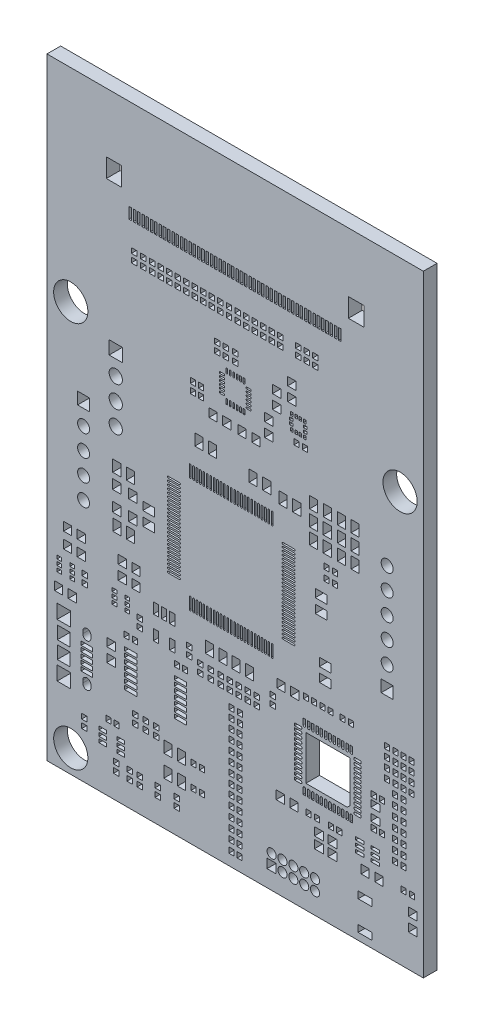
SolidWorks part; units mm, degrees
ref_plane "Plan de face" through (0, 0, 0) normal (0, 0, 1) x (1, 0, 0)
ref_plane "Plan de dessus" through (0, 0, 0) normal (0, 1, 0) x (1, 0, 0)
ref_plane "Plan de droite" through (0, 0, 0) normal (1, 0, 0) x (0, 0, -1)
sketch "Model" plane through (0, 0, 0) normal (0, 0, 1) x (1, 0, 0)
  line L0 (49.4, 104.5) -> (49.9, 104.5)
  line L1 (49.9, 104.3) -> (49.4, 104.3)
  line L2 (49.4, 104.3) -> (49.4, 104.5)
  line L3 (49.4, 104.1) -> (49.9, 104.1)
  line L4 (49.9, 103.9) -> (49.4, 103.9)
  line L5 (49.4, 103.9) -> (49.4, 104.1)
  line L6 (49.4, 103.7) -> (49.9, 103.7)
  line L7 (49.9, 103.5) -> (49.4, 103.5)
  line L8 (49.4, 103.5) -> (49.4, 103.7)
  line L9 (49.4, 103.3) -> (49.9, 103.3)
  line L10 (49.9, 103.1) -> (49.4, 103.1)
  line L11 (49.4, 103.1) -> (49.4, 103.3)
  line L12 (49.4, 102.9) -> (49.9, 102.9)
  line L13 (49.9, 102.7) -> (49.4, 102.7)
  line L14 (49.4, 102.7) -> (49.4, 102.9)
  line L15 (49.4, 102.5) -> (49.9, 102.5)
  line L16 (49.9, 102.3) -> (49.4, 102.3)
  line L17 (49.4, 102.3) -> (49.4, 102.5)
  line L18 (50.15, 101.55) -> (50.15, 102.05)
  line L19 (50.35, 102.05) -> (50.35, 101.55)
  line L20 (50.35, 101.55) -> (50.15, 101.55)
  line L21 (50.55, 101.55) -> (50.55, 102.05)
  line L22 (50.75, 102.05) -> (50.75, 101.55)
  line L23 (50.75, 101.55) -> (50.55, 101.55)
  line L24 (50.95, 101.55) -> (50.95, 102.05)
  line L25 (51.15, 102.05) -> (51.15, 101.55)
  line L26 (51.15, 101.55) -> (50.95, 101.55)
  line L27 (51.35, 101.55) -> (51.35, 102.05)
  line L28 (51.55, 102.05) -> (51.55, 101.55)
  line L29 (51.55, 101.55) -> (51.35, 101.55)
  line L30 (51.75, 101.55) -> (51.75, 102.05)
  line L31 (51.95, 102.05) -> (51.95, 101.55)
  line L32 (51.95, 101.55) -> (51.75, 101.55)
  line L33 (52.15, 101.55) -> (52.15, 102.05)
  line L34 (52.35, 102.05) -> (52.35, 101.55)
  line L35 (52.35, 101.55) -> (52.15, 101.55)
  line L36 (53.1, 102.3) -> (52.6, 102.3)
  line L37 (52.6, 102.5) -> (53.1, 102.5)
  line L38 (53.1, 102.5) -> (53.1, 102.3)
  line L39 (53.1, 102.7) -> (52.6, 102.7)
  line L40 (52.6, 102.9) -> (53.1, 102.9)
  line L41 (53.1, 102.9) -> (53.1, 102.7)
  line L42 (53.1, 103.1) -> (52.6, 103.1)
  line L43 (52.6, 103.3) -> (53.1, 103.3)
  line L44 (53.1, 103.3) -> (53.1, 103.1)
  line L45 (53.1, 103.5) -> (52.6, 103.5)
  line L46 (52.6, 103.7) -> (53.1, 103.7)
  line L47 (53.1, 103.7) -> (53.1, 103.5)
  line L48 (53.1, 103.9) -> (52.6, 103.9)
  line L49 (52.6, 104.1) -> (53.1, 104.1)
  line L50 (53.1, 104.1) -> (53.1, 103.9)
  line L51 (53.1, 104.3) -> (52.6, 104.3)
  line L52 (52.6, 104.5) -> (53.1, 104.5)
  line L53 (53.1, 104.5) -> (53.1, 104.3)
  line L54 (52.35, 105.25) -> (52.35, 104.75)
  line L55 (52.15, 104.75) -> (52.15, 105.25)
  line L56 (52.15, 105.25) -> (52.35, 105.25)
  line L57 (51.95, 105.25) -> (51.95, 104.75)
  line L58 (51.75, 104.75) -> (51.75, 105.25)
  line L59 (51.75, 105.25) -> (51.95, 105.25)
  line L60 (51.55, 105.25) -> (51.55, 104.75)
  line L61 (51.35, 104.75) -> (51.35, 105.25)
  line L62 (51.35, 105.25) -> (51.55, 105.25)
  line L63 (51.15, 105.25) -> (51.15, 104.75)
  line L64 (50.95, 104.75) -> (50.95, 105.25)
  line L65 (50.95, 105.25) -> (51.15, 105.25)
  line L66 (50.75, 105.25) -> (50.75, 104.75)
  line L67 (50.55, 104.75) -> (50.55, 105.25)
  line L68 (50.55, 105.25) -> (50.75, 105.25)
  line L69 (50.35, 105.25) -> (50.35, 104.75)
  line L70 (50.15, 104.75) -> (50.15, 105.25)
  line L71 (50.15, 105.25) -> (50.35, 105.25)
  line L72 (59.2, 104.6) -> (59.5, 104.6)
  line L73 (59.5, 104.6) -> (59.5, 104.2)
  line L74 (59.5, 104.2) -> (59.2, 104.2)
  line L75 (59.2, 104.2) -> (59.2, 104.6)
  line L76 (58.7, 104.6) -> (59, 104.6)
  line L77 (59, 104.6) -> (59, 104.2)
  line L78 (59, 104.2) -> (58.7, 104.2)
  line L79 (58.7, 104.2) -> (58.7, 104.6)
  line L80 (58.2, 104.6) -> (58.5, 104.6)
  line L81 (58.5, 104.6) -> (58.5, 104.2)
  line L82 (58.5, 104.2) -> (58.2, 104.2)
  line L83 (58.2, 104.2) -> (58.2, 104.6)
  line L84 (57.7, 104.6) -> (58, 104.6)
  line L85 (58, 104.6) -> (58, 104.2)
  line L86 (58, 104.2) -> (57.7, 104.2)
  line L87 (57.7, 104.2) -> (57.7, 104.6)
  line L88 (57.6, 103.7) -> (57.6, 104)
  line L89 (57.6, 104) -> (58, 104)
  line L90 (58, 104) -> (58, 103.7)
  line L91 (58, 103.7) -> (57.6, 103.7)
  line L92 (57.6, 103.2) -> (57.6, 103.5)
  line L93 (57.6, 103.5) -> (58, 103.5)
  line L94 (58, 103.5) -> (58, 103.2)
  line L95 (58, 103.2) -> (57.6, 103.2)
  line L96 (57.7, 103) -> (58, 103)
  line L97 (58, 103) -> (58, 102.6)
  line L98 (58, 102.6) -> (57.7, 102.6)
  line L99 (57.7, 102.6) -> (57.7, 103)
  line L100 (58.2, 103) -> (58.5, 103)
  line L101 (58.5, 103) -> (58.5, 102.6)
  line L102 (58.5, 102.6) -> (58.2, 102.6)
  line L103 (58.2, 102.6) -> (58.2, 103)
  line L104 (58.7, 103) -> (59, 103)
  line L105 (59, 103) -> (59, 102.6)
  line L106 (59, 102.6) -> (58.7, 102.6)
  line L107 (58.7, 102.6) -> (58.7, 103)
  line L108 (59.2, 103) -> (59.5, 103)
  line L109 (59.5, 103) -> (59.5, 102.6)
  line L110 (59.5, 102.6) -> (59.2, 102.6)
  line L111 (59.2, 102.6) -> (59.2, 103)
  line L112 (59.2, 103.2) -> (59.2, 103.5)
  line L113 (59.2, 103.5) -> (59.6, 103.5)
  line L114 (59.6, 103.5) -> (59.6, 103.2)
  line L115 (59.6, 103.2) -> (59.2, 103.2)
  line L116 (59.2, 103.7) -> (59.2, 104)
  line L117 (59.2, 104) -> (59.6, 104)
  line L118 (59.6, 104) -> (59.6, 103.7)
  line L119 (59.6, 103.7) -> (59.2, 103.7)
  line L120 (35.3, 61.15) -> (35.3, 61.55)
  line L121 (35.3, 61.55) -> (36.2, 61.55)
  line L122 (36.2, 61.55) -> (36.2, 61.15)
  line L123 (36.2, 61.15) -> (35.3, 61.15)
  line L124 (35.3, 60.5) -> (35.3, 60.9)
  line L125 (35.3, 60.9) -> (36.2, 60.9)
  line L126 (36.2, 60.9) -> (36.2, 60.5)
  line L127 (36.2, 60.5) -> (35.3, 60.5)
  line L128 (35.3, 59.85) -> (35.3, 60.25)
  line L129 (35.3, 60.25) -> (36.2, 60.25)
  line L130 (36.2, 60.25) -> (36.2, 59.85)
  line L131 (36.2, 59.85) -> (35.3, 59.85)
  line L132 (37.4, 59.85) -> (37.4, 60.25)
  line L133 (37.4, 60.25) -> (38.3, 60.25)
  line L134 (38.3, 60.25) -> (38.3, 59.85)
  line L135 (38.3, 59.85) -> (37.4, 59.85)
  line L136 (37.4, 60.5) -> (37.4, 60.9)
  line L137 (37.4, 60.9) -> (38.3, 60.9)
  line L138 (38.3, 60.9) -> (38.3, 60.5)
  line L139 (38.3, 60.5) -> (37.4, 60.5)
  line L140 (37.4, 61.15) -> (37.4, 61.55)
  line L141 (37.4, 61.55) -> (38.3, 61.55)
  line L142 (38.3, 61.55) -> (38.3, 61.15)
  line L143 (38.3, 61.15) -> (37.4, 61.15)
  line L144 (39.1105, 115.9042) -> (39.1105, 114.6042)
  line L145 (39.1105, 114.6042) -> (38.8105, 114.6042)
  line L146 (38.8105, 114.6042) -> (38.8105, 115.9042)
  line L147 (38.8105, 115.9042) -> (39.1105, 115.9042)
  line L148 (39.6105, 115.9042) -> (39.6105, 114.6042)
  line L149 (39.6105, 114.6042) -> (39.3105, 114.6042)
  line L150 (39.3105, 114.6042) -> (39.3105, 115.9042)
  line L151 (39.3105, 115.9042) -> (39.6105, 115.9042)
  line L152 (40.1105, 115.9042) -> (40.1105, 114.6042)
  line L153 (40.1105, 114.6042) -> (39.8105, 114.6042)
  line L154 (39.8105, 114.6042) -> (39.8105, 115.9042)
  line L155 (39.8105, 115.9042) -> (40.1105, 115.9042)
  line L156 (40.6105, 115.9042) -> (40.6105, 114.6042)
  line L157 (40.6105, 114.6042) -> (40.3105, 114.6042)
  line L158 (40.3105, 114.6042) -> (40.3105, 115.9042)
  line L159 (40.3105, 115.9042) -> (40.6105, 115.9042)
  line L160 (41.1105, 115.9042) -> (41.1105, 114.6042)
  line L161 (41.1105, 114.6042) -> (40.8105, 114.6042)
  line L162 (40.8105, 114.6042) -> (40.8105, 115.9042)
  line L163 (40.8105, 115.9042) -> (41.1105, 115.9042)
  line L164 (41.6105, 115.9042) -> (41.6105, 114.6042)
  line L165 (41.6105, 114.6042) -> (41.3105, 114.6042)
  line L166 (41.3105, 114.6042) -> (41.3105, 115.9042)
  line L167 (41.3105, 115.9042) -> (41.6105, 115.9042)
  line L168 (42.1105, 115.9042) -> (42.1105, 114.6042)
  line L169 (42.1105, 114.6042) -> (41.8105, 114.6042)
  line L170 (41.8105, 114.6042) -> (41.8105, 115.9042)
  line L171 (41.8105, 115.9042) -> (42.1105, 115.9042)
  line L172 (42.6105, 115.9042) -> (42.6105, 114.6042)
  line L173 (42.6105, 114.6042) -> (42.3105, 114.6042)
  line L174 (42.3105, 114.6042) -> (42.3105, 115.9042)
  line L175 (42.3105, 115.9042) -> (42.6105, 115.9042)
  line L176 (43.1105, 115.9042) -> (43.1105, 114.6042)
  line L177 (43.1105, 114.6042) -> (42.8105, 114.6042)
  line L178 (42.8105, 114.6042) -> (42.8105, 115.9042)
  line L179 (42.8105, 115.9042) -> (43.1105, 115.9042)
  line L180 (43.6105, 115.9042) -> (43.6105, 114.6042)
  line L181 (43.6105, 114.6042) -> (43.3105, 114.6042)
  line L182 (43.3105, 114.6042) -> (43.3105, 115.9042)
  line L183 (43.3105, 115.9042) -> (43.6105, 115.9042)
  line L184 (44.1105, 115.9042) -> (44.1105, 114.6042)
  line L185 (44.1105, 114.6042) -> (43.8105, 114.6042)
  line L186 (43.8105, 114.6042) -> (43.8105, 115.9042)
  line L187 (43.8105, 115.9042) -> (44.1105, 115.9042)
  line L188 (44.6105, 115.9042) -> (44.6105, 114.6042)
  line L189 (44.6105, 114.6042) -> (44.3105, 114.6042)
  line L190 (44.3105, 114.6042) -> (44.3105, 115.9042)
  line L191 (44.3105, 115.9042) -> (44.6105, 115.9042)
  line L192 (45.1105, 115.9042) -> (45.1105, 114.6042)
  line L193 (45.1105, 114.6042) -> (44.8105, 114.6042)
  line L194 (44.8105, 114.6042) -> (44.8105, 115.9042)
  line L195 (44.8105, 115.9042) -> (45.1105, 115.9042)
  line L196 (45.6105, 115.9042) -> (45.6105, 114.6042)
  line L197 (45.6105, 114.6042) -> (45.3105, 114.6042)
  line L198 (45.3105, 114.6042) -> (45.3105, 115.9042)
  line L199 (45.3105, 115.9042) -> (45.6105, 115.9042)
  line L200 (46.1105, 115.9042) -> (46.1105, 114.6042)
  line L201 (46.1105, 114.6042) -> (45.8105, 114.6042)
  line L202 (45.8105, 114.6042) -> (45.8105, 115.9042)
  line L203 (45.8105, 115.9042) -> (46.1105, 115.9042)
  line L204 (46.6105, 115.9042) -> (46.6105, 114.6042)
  line L205 (46.6105, 114.6042) -> (46.3105, 114.6042)
  line L206 (46.3105, 114.6042) -> (46.3105, 115.9042)
  line L207 (46.3105, 115.9042) -> (46.6105, 115.9042)
  line L208 (47.1105, 115.9042) -> (47.1105, 114.6042)
  line L209 (47.1105, 114.6042) -> (46.8105, 114.6042)
  line L210 (46.8105, 114.6042) -> (46.8105, 115.9042)
  line L211 (46.8105, 115.9042) -> (47.1105, 115.9042)
  line L212 (47.6105, 115.9042) -> (47.6105, 114.6042)
  line L213 (47.6105, 114.6042) -> (47.3105, 114.6042)
  line L214 (47.3105, 114.6042) -> (47.3105, 115.9042)
  line L215 (47.3105, 115.9042) -> (47.6105, 115.9042)
  line L216 (48.1105, 115.9042) -> (48.1105, 114.6042)
  line L217 (48.1105, 114.6042) -> (47.8105, 114.6042)
  line L218 (47.8105, 114.6042) -> (47.8105, 115.9042)
  line L219 (47.8105, 115.9042) -> (48.1105, 115.9042)
  line L220 (48.6105, 115.9042) -> (48.6105, 114.6042)
  line L221 (48.6105, 114.6042) -> (48.3105, 114.6042)
  line L222 (48.3105, 114.6042) -> (48.3105, 115.9042)
  line L223 (48.3105, 115.9042) -> (48.6105, 115.9042)
  line L224 (49.1105, 115.9042) -> (49.1105, 114.6042)
  line L225 (49.1105, 114.6042) -> (48.8105, 114.6042)
  line L226 (48.8105, 114.6042) -> (48.8105, 115.9042)
  line L227 (48.8105, 115.9042) -> (49.1105, 115.9042)
  line L228 (49.6105, 115.9042) -> (49.6105, 114.6042)
  line L229 (49.6105, 114.6042) -> (49.3105, 114.6042)
  line L230 (49.3105, 114.6042) -> (49.3105, 115.9042)
  line L231 (49.3105, 115.9042) -> (49.6105, 115.9042)
  line L232 (50.1105, 115.9042) -> (50.1105, 114.6042)
  line L233 (50.1105, 114.6042) -> (49.8105, 114.6042)
  line L234 (49.8105, 114.6042) -> (49.8105, 115.9042)
  line L235 (49.8105, 115.9042) -> (50.1105, 115.9042)
  line L236 (50.6105, 115.9042) -> (50.6105, 114.6042)
  line L237 (50.6105, 114.6042) -> (50.3105, 114.6042)
  line L238 (50.3105, 114.6042) -> (50.3105, 115.9042)
  line L239 (50.3105, 115.9042) -> (50.6105, 115.9042)
  line L240 (51.1105, 115.9042) -> (51.1105, 114.6042)
  line L241 (51.1105, 114.6042) -> (50.8105, 114.6042)
  line L242 (50.8105, 114.6042) -> (50.8105, 115.9042)
  line L243 (50.8105, 115.9042) -> (51.1105, 115.9042)
  line L244 (51.6105, 115.9042) -> (51.6105, 114.6042)
  line L245 (51.6105, 114.6042) -> (51.3105, 114.6042)
  line L246 (51.3105, 114.6042) -> (51.3105, 115.9042)
  line L247 (51.3105, 115.9042) -> (51.6105, 115.9042)
  line L248 (52.1105, 115.9042) -> (52.1105, 114.6042)
  line L249 (52.1105, 114.6042) -> (51.8105, 114.6042)
  line L250 (51.8105, 114.6042) -> (51.8105, 115.9042)
  line L251 (51.8105, 115.9042) -> (52.1105, 115.9042)
  line L252 (52.6105, 115.9042) -> (52.6105, 114.6042)
  line L253 (52.6105, 114.6042) -> (52.3105, 114.6042)
  line L254 (52.3105, 114.6042) -> (52.3105, 115.9042)
  line L255 (52.3105, 115.9042) -> (52.6105, 115.9042)
  line L256 (53.1105, 115.9042) -> (53.1105, 114.6042)
  line L257 (53.1105, 114.6042) -> (52.8105, 114.6042)
  line L258 (52.8105, 114.6042) -> (52.8105, 115.9042)
  line L259 (52.8105, 115.9042) -> (53.1105, 115.9042)
  line L260 (53.6105, 115.9042) -> (53.6105, 114.6042)
  line L261 (53.6105, 114.6042) -> (53.3105, 114.6042)
  line L262 (53.3105, 114.6042) -> (53.3105, 115.9042)
  line L263 (53.3105, 115.9042) -> (53.6105, 115.9042)
  line L264 (54.1105, 115.9042) -> (54.1105, 114.6042)
  line L265 (54.1105, 114.6042) -> (53.8105, 114.6042)
  line L266 (53.8105, 114.6042) -> (53.8105, 115.9042)
  line L267 (53.8105, 115.9042) -> (54.1105, 115.9042)
  line L268 (54.6105, 115.9042) -> (54.6105, 114.6042)
  line L269 (54.6105, 114.6042) -> (54.3105, 114.6042)
  line L270 (54.3105, 114.6042) -> (54.3105, 115.9042)
  line L271 (54.3105, 115.9042) -> (54.6105, 115.9042)
  line L272 (55.1105, 115.9042) -> (55.1105, 114.6042)
  line L273 (55.1105, 114.6042) -> (54.8105, 114.6042)
  line L274 (54.8105, 114.6042) -> (54.8105, 115.9042)
  line L275 (54.8105, 115.9042) -> (55.1105, 115.9042)
  line L276 (55.6105, 115.9042) -> (55.6105, 114.6042)
  line L277 (55.6105, 114.6042) -> (55.3105, 114.6042)
  line L278 (55.3105, 114.6042) -> (55.3105, 115.9042)
  line L279 (55.3105, 115.9042) -> (55.6105, 115.9042)
  line L280 (56.1105, 115.9042) -> (56.1105, 114.6042)
  line L281 (56.1105, 114.6042) -> (55.8105, 114.6042)
  line L282 (55.8105, 114.6042) -> (55.8105, 115.9042)
  line L283 (55.8105, 115.9042) -> (56.1105, 115.9042)
  line L284 (56.6105, 115.9042) -> (56.6105, 114.6042)
  line L285 (56.6105, 114.6042) -> (56.3105, 114.6042)
  line L286 (56.3105, 114.6042) -> (56.3105, 115.9042)
  line L287 (56.3105, 115.9042) -> (56.6105, 115.9042)
  line L288 (57.1105, 115.9042) -> (57.1105, 114.6042)
  line L289 (57.1105, 114.6042) -> (56.8105, 114.6042)
  line L290 (56.8105, 114.6042) -> (56.8105, 115.9042)
  line L291 (56.8105, 115.9042) -> (57.1105, 115.9042)
  line L292 (57.6105, 115.9042) -> (57.6105, 114.6042)
  line L293 (57.6105, 114.6042) -> (57.3105, 114.6042)
  line L294 (57.3105, 114.6042) -> (57.3105, 115.9042)
  line L295 (57.3105, 115.9042) -> (57.6105, 115.9042)
  line L296 (58.1105, 115.9042) -> (58.1105, 114.6042)
  line L297 (58.1105, 114.6042) -> (57.8105, 114.6042)
  line L298 (57.8105, 114.6042) -> (57.8105, 115.9042)
  line L299 (57.8105, 115.9042) -> (58.1105, 115.9042)
  line L300 (58.6105, 115.9042) -> (58.6105, 114.6042)
  line L301 (58.6105, 114.6042) -> (58.3105, 114.6042)
  line L302 (58.3105, 114.6042) -> (58.3105, 115.9042)
  line L303 (58.3105, 115.9042) -> (58.6105, 115.9042)
  line L304 (59.1105, 115.9042) -> (59.1105, 114.6042)
  line L305 (59.1105, 114.6042) -> (58.8105, 114.6042)
  line L306 (58.8105, 114.6042) -> (58.8105, 115.9042)
  line L307 (58.8105, 115.9042) -> (59.1105, 115.9042)
  line L308 (59.6105, 115.9042) -> (59.6105, 114.6042)
  line L309 (59.6105, 114.6042) -> (59.3105, 114.6042)
  line L310 (59.3105, 114.6042) -> (59.3105, 115.9042)
  line L311 (59.3105, 115.9042) -> (59.6105, 115.9042)
  line L312 (60.1105, 115.9042) -> (60.1105, 114.6042)
  line L313 (60.1105, 114.6042) -> (59.8105, 114.6042)
  line L314 (59.8105, 114.6042) -> (59.8105, 115.9042)
  line L315 (59.8105, 115.9042) -> (60.1105, 115.9042)
  line L316 (60.6105, 115.9042) -> (60.6105, 114.6042)
  line L317 (60.6105, 114.6042) -> (60.3105, 114.6042)
  line L318 (60.3105, 114.6042) -> (60.3105, 115.9042)
  line L319 (60.3105, 115.9042) -> (60.6105, 115.9042)
  line L320 (61.1105, 115.9042) -> (61.1105, 114.6042)
  line L321 (61.1105, 114.6042) -> (60.8105, 114.6042)
  line L322 (60.8105, 114.6042) -> (60.8105, 115.9042)
  line L323 (60.8105, 115.9042) -> (61.1105, 115.9042)
  line L324 (61.6105, 115.9042) -> (61.6105, 114.6042)
  line L325 (61.6105, 114.6042) -> (61.3105, 114.6042)
  line L326 (61.3105, 114.6042) -> (61.3105, 115.9042)
  line L327 (61.3105, 115.9042) -> (61.6105, 115.9042)
  line L328 (62.1105, 115.9042) -> (62.1105, 114.6042)
  line L329 (62.1105, 114.6042) -> (61.8105, 114.6042)
  line L330 (61.8105, 114.6042) -> (61.8105, 115.9042)
  line L331 (61.8105, 115.9042) -> (62.1105, 115.9042)
  line L332 (62.6105, 115.9042) -> (62.6105, 114.6042)
  line L333 (62.6105, 114.6042) -> (62.3105, 114.6042)
  line L334 (62.3105, 114.6042) -> (62.3105, 115.9042)
  line L335 (62.3105, 115.9042) -> (62.6105, 115.9042)
  line L336 (63.1105, 115.9042) -> (63.1105, 114.6042)
  line L337 (63.1105, 114.6042) -> (62.8105, 114.6042)
  line L338 (62.8105, 114.6042) -> (62.8105, 115.9042)
  line L339 (62.8105, 115.9042) -> (63.1105, 115.9042)
  line L340 (63.6105, 115.9042) -> (63.6105, 114.6042)
  line L341 (63.6105, 114.6042) -> (63.3105, 114.6042)
  line L342 (63.3105, 114.6042) -> (63.3105, 115.9042)
  line L343 (63.3105, 115.9042) -> (63.6105, 115.9042)
  line L344 (37.9605, 119.6042) -> (37.9605, 117.4042)
  line L345 (37.9605, 117.4042) -> (36.1605, 117.4042)
  line L346 (36.1605, 117.4042) -> (36.1605, 119.6042)
  line L347 (36.1605, 119.6042) -> (37.9605, 119.6042)
  line L348 (66.2605, 119.6042) -> (66.2605, 117.4042)
  line L349 (66.2605, 117.4042) -> (64.4605, 117.4042)
  line L350 (64.4605, 117.4042) -> (64.4605, 119.6042)
  line L351 (64.4605, 119.6042) -> (66.2605, 119.6042)
  line L352 (38.035, 101.245) -> (36.485, 101.245)
  line L353 (36.485, 101.245) -> (36.485, 99.695)
  line L354 (36.485, 99.695) -> (38.035, 99.695)
  line L355 (38.035, 99.695) -> (38.035, 101.245)
  line L356 (69.69, 81.41) -> (68.29, 81.41)
  line L357 (68.29, 81.41) -> (68.29, 82.81)
  line L358 (68.29, 82.81) -> (69.69, 82.81)
  line L359 (69.69, 82.81) -> (69.69, 81.41)
  line L360 (38.77, 87.39) -> (39.77, 87.39)
  line L361 (39.77, 87.39) -> (39.77, 86.29)
  line L362 (39.77, 86.29) -> (38.77, 86.29)
  line L363 (38.77, 86.29) -> (38.77, 87.39)
  line L364 (36.87, 87.39) -> (37.87, 87.39)
  line L365 (37.87, 87.39) -> (37.87, 86.29)
  line L366 (37.87, 86.29) -> (36.87, 86.29)
  line L367 (36.87, 86.29) -> (36.87, 87.39)
  line L368 (36.87, 85.09) -> (37.87, 85.09)
  line L369 (37.87, 85.09) -> (37.87, 83.99)
  line L370 (37.87, 83.99) -> (36.87, 83.99)
  line L371 (36.87, 83.99) -> (36.87, 85.09)
  line L372 (38.77, 85.09) -> (39.77, 85.09)
  line L373 (39.77, 85.09) -> (39.77, 83.99)
  line L374 (39.77, 83.99) -> (38.77, 83.99)
  line L375 (38.77, 83.99) -> (38.77, 85.09)
  line L376 (36.845, 75.94) -> (36.845, 76.34)
  line L377 (36.845, 76.34) -> (37.395, 76.34)
  line L378 (37.395, 76.34) -> (37.395, 75.94)
  line L379 (37.395, 75.94) -> (36.845, 75.94)
  line L380 (36.845, 75.29) -> (36.845, 75.69)
  line L381 (36.845, 75.69) -> (37.395, 75.69)
  line L382 (37.395, 75.69) -> (37.395, 75.29)
  line L383 (37.395, 75.29) -> (36.845, 75.29)
  line L384 (36.845, 74.64) -> (36.845, 75.04)
  line L385 (36.845, 75.04) -> (37.395, 75.04)
  line L386 (37.395, 75.04) -> (37.395, 74.64)
  line L387 (37.395, 74.64) -> (36.845, 74.64)
  line L388 (38.345, 74.64) -> (38.345, 75.04)
  line L389 (38.345, 75.04) -> (38.895, 75.04)
  line L390 (38.895, 75.04) -> (38.895, 74.64)
  line L391 (38.895, 74.64) -> (38.345, 74.64)
  line L392 (38.345, 75.29) -> (38.345, 75.69)
  line L393 (38.345, 75.69) -> (38.895, 75.69)
  line L394 (38.895, 75.69) -> (38.895, 75.29)
  line L395 (38.895, 75.29) -> (38.345, 75.29)
  line L396 (38.345, 75.94) -> (38.345, 76.34)
  line L397 (38.345, 76.34) -> (38.895, 76.34)
  line L398 (38.895, 76.34) -> (38.895, 75.94)
  line L399 (38.895, 75.94) -> (38.345, 75.94)
  line L400 (30.395, 76) -> (30.395, 76.4)
  line L401 (30.395, 76.4) -> (30.945, 76.4)
  line L402 (30.945, 76.4) -> (30.945, 76)
  line L403 (30.945, 76) -> (30.395, 76)
  line L404 (30.395, 75.35) -> (30.395, 75.75)
  line L405 (30.395, 75.75) -> (30.945, 75.75)
  line L406 (30.945, 75.75) -> (30.945, 75.35)
  line L407 (30.945, 75.35) -> (30.395, 75.35)
  line L408 (30.395, 74.7) -> (30.395, 75.1)
  line L409 (30.395, 75.1) -> (30.945, 75.1)
  line L410 (30.945, 75.1) -> (30.945, 74.7)
  line L411 (30.945, 74.7) -> (30.395, 74.7)
  line L412 (31.895, 74.7) -> (31.895, 75.1)
  line L413 (31.895, 75.1) -> (32.445, 75.1)
  line L414 (32.445, 75.1) -> (32.445, 74.7)
  line L415 (32.445, 74.7) -> (31.895, 74.7)
  line L416 (31.895, 75.35) -> (31.895, 75.75)
  line L417 (31.895, 75.75) -> (32.445, 75.75)
  line L418 (32.445, 75.75) -> (32.445, 75.35)
  line L419 (32.445, 75.35) -> (31.895, 75.35)
  line L420 (31.895, 76) -> (31.895, 76.4)
  line L421 (31.895, 76.4) -> (32.445, 76.4)
  line L422 (32.445, 76.4) -> (32.445, 76)
  line L423 (32.445, 76) -> (31.895, 76)
  line L424 (45.555, 67.175) -> (45.555, 66.725)
  line L425 (45.555, 66.725) -> (44.105, 66.725)
  line L426 (44.105, 66.725) -> (44.105, 67.175)
  line L427 (44.105, 67.175) -> (45.555, 67.175)
  line L428 (45.555, 67.825) -> (45.555, 67.375)
  line L429 (45.555, 67.375) -> (44.105, 67.375)
  line L430 (44.105, 67.375) -> (44.105, 67.825)
  line L431 (44.105, 67.825) -> (45.555, 67.825)
  line L432 (45.555, 68.475) -> (45.555, 68.025)
  line L433 (45.555, 68.025) -> (44.105, 68.025)
  line L434 (44.105, 68.025) -> (44.105, 68.475)
  line L435 (44.105, 68.475) -> (45.555, 68.475)
  line L436 (45.555, 69.125) -> (45.555, 68.675)
  line L437 (45.555, 68.675) -> (44.105, 68.675)
  line L438 (44.105, 68.675) -> (44.105, 69.125)
  line L439 (44.105, 69.125) -> (45.555, 69.125)
  line L440 (45.555, 69.775) -> (45.555, 69.325)
  line L441 (45.555, 69.325) -> (44.105, 69.325)
  line L442 (44.105, 69.325) -> (44.105, 69.775)
  line L443 (44.105, 69.775) -> (45.555, 69.775)
  line L444 (45.555, 70.425) -> (45.555, 69.975)
  line L445 (45.555, 69.975) -> (44.105, 69.975)
  line L446 (44.105, 69.975) -> (44.105, 70.425)
  line L447 (44.105, 70.425) -> (45.555, 70.425)
  line L448 (45.555, 71.075) -> (45.555, 70.625)
  line L449 (45.555, 70.625) -> (44.105, 70.625)
  line L450 (44.105, 70.625) -> (44.105, 71.075)
  line L451 (44.105, 71.075) -> (45.555, 71.075)
  line L452 (39.755, 71.075) -> (39.755, 70.625)
  line L453 (39.755, 70.625) -> (38.305, 70.625)
  line L454 (38.305, 70.625) -> (38.305, 71.075)
  line L455 (38.305, 71.075) -> (39.755, 71.075)
  line L456 (39.755, 70.425) -> (39.755, 69.975)
  line L457 (39.755, 69.975) -> (38.305, 69.975)
  line L458 (38.305, 69.975) -> (38.305, 70.425)
  line L459 (38.305, 70.425) -> (39.755, 70.425)
  line L460 (39.755, 69.775) -> (39.755, 69.325)
  line L461 (39.755, 69.325) -> (38.305, 69.325)
  line L462 (38.305, 69.325) -> (38.305, 69.775)
  line L463 (38.305, 69.775) -> (39.755, 69.775)
  line L464 (39.755, 69.125) -> (39.755, 68.675)
  line L465 (39.755, 68.675) -> (38.305, 68.675)
  line L466 (38.305, 68.675) -> (38.305, 69.125)
  line L467 (38.305, 69.125) -> (39.755, 69.125)
  line L468 (39.755, 68.475) -> (39.755, 68.025)
  line L469 (39.755, 68.025) -> (38.305, 68.025)
  line L470 (38.305, 68.025) -> (38.305, 68.475)
  line L471 (38.305, 68.475) -> (39.755, 68.475)
  line L472 (39.755, 67.825) -> (39.755, 67.375)
  line L473 (39.755, 67.375) -> (38.305, 67.375)
  line L474 (38.305, 67.375) -> (38.305, 67.825)
  line L475 (38.305, 67.825) -> (39.755, 67.825)
  line L476 (39.755, 67.175) -> (39.755, 66.725)
  line L477 (39.755, 66.725) -> (38.305, 66.725)
  line L478 (38.305, 66.725) -> (38.305, 67.175)
  line L479 (38.305, 67.175) -> (39.755, 67.175)
  line L480 (43.56, 77.305) -> (44.16, 77.305)
  line L481 (44.16, 77.305) -> (44.16, 76.055)
  line L482 (44.16, 76.055) -> (43.56, 76.055)
  line L483 (43.56, 76.055) -> (43.56, 77.305)
  line L484 (42.61, 77.305) -> (43.21, 77.305)
  line L485 (43.21, 77.305) -> (43.21, 76.055)
  line L486 (43.21, 76.055) -> (42.61, 76.055)
  line L487 (42.61, 76.055) -> (42.61, 77.305)
  line L488 (41.66, 77.305) -> (42.26, 77.305)
  line L489 (42.26, 77.305) -> (42.26, 76.055)
  line L490 (42.26, 76.055) -> (41.66, 76.055)
  line L491 (41.66, 76.055) -> (41.66, 77.305)
  line L492 (41.66, 74.605) -> (42.26, 74.605)
  line L493 (42.26, 74.605) -> (42.26, 73.355)
  line L494 (42.26, 73.355) -> (41.66, 73.355)
  line L495 (41.66, 73.355) -> (41.66, 74.605)
  line L496 (43.56, 74.605) -> (44.16, 74.605)
  line L497 (44.16, 74.605) -> (44.16, 73.355)
  line L498 (44.16, 73.355) -> (43.56, 73.355)
  line L499 (43.56, 73.355) -> (43.56, 74.605)
  line L500 (31.955, 65.2905) -> (31.955, 63.6455)
  line L501 (31.955, 63.6455) -> (30.405, 63.6455)
  line L502 (30.405, 63.6455) -> (30.405, 65.2905)
  line L503 (30.405, 65.2905) -> (31.955, 65.2905)
  line L504 (30.405, 69.8895) -> (30.405, 71.5345)
  line L505 (30.405, 71.5345) -> (31.955, 71.5345)
  line L506 (31.955, 71.5345) -> (31.955, 69.8895)
  line L507 (31.955, 69.8895) -> (30.405, 69.8895)
  line L508 (34.355, 65.24) -> (34.355, 64.94)
  line L509 (33.405, 64.94) -> (33.405, 65.24)
  line L510 (34.355, 70.24) -> (34.355, 69.94)
  line L511 (33.405, 69.94) -> (33.405, 70.24)
  line L512 (33.205, 66.065) -> (33.205, 66.515)
  line L513 (33.205, 66.515) -> (34.555, 66.515)
  line L514 (34.555, 66.515) -> (34.555, 66.065)
  line L515 (34.555, 66.065) -> (33.205, 66.065)
  line L516 (33.205, 66.715) -> (33.205, 67.165)
  line L517 (33.205, 67.165) -> (34.555, 67.165)
  line L518 (34.555, 67.165) -> (34.555, 66.715)
  line L519 (34.555, 66.715) -> (33.205, 66.715)
  line L520 (33.205, 67.365) -> (33.205, 67.815)
  line L521 (33.205, 67.815) -> (34.555, 67.815)
  line L522 (34.555, 67.815) -> (34.555, 67.365)
  line L523 (34.555, 67.365) -> (33.205, 67.365)
  line L524 (33.205, 68.015) -> (33.205, 68.465)
  line L525 (33.205, 68.465) -> (34.555, 68.465)
  line L526 (34.555, 68.465) -> (34.555, 68.015)
  line L527 (34.555, 68.015) -> (33.205, 68.015)
  line L528 (33.205, 68.665) -> (33.205, 69.115)
  line L529 (33.205, 69.115) -> (34.555, 69.115)
  line L530 (34.555, 69.115) -> (34.555, 68.665)
  line L531 (34.555, 68.665) -> (33.205, 68.665)
  line L532 (30.43, 65.84) -> (30.43, 67.34)
  line L533 (30.43, 67.34) -> (31.93, 67.34)
  line L534 (31.93, 67.34) -> (31.93, 65.84)
  line L535 (31.93, 65.84) -> (30.43, 65.84)
  line L536 (30.43, 67.84) -> (30.43, 69.34)
  line L537 (30.43, 69.34) -> (31.93, 69.34)
  line L538 (31.93, 69.34) -> (31.93, 67.84)
  line L539 (31.93, 67.84) -> (30.43, 67.84)
  line L540 (61.065, 80.445) -> (61.065, 81.395)
  line L541 (61.065, 81.395) -> (62.415, 81.395)
  line L542 (62.415, 81.395) -> (62.415, 80.445)
  line L543 (62.415, 80.445) -> (61.065, 80.445)
  line L544 (61.065, 78.845) -> (61.065, 79.795)
  line L545 (61.065, 79.795) -> (62.415, 79.795)
  line L546 (62.415, 79.795) -> (62.415, 78.845)
  line L547 (62.415, 78.845) -> (61.065, 78.845)
  line L548 (40.425, 85.925) -> (40.425, 86.875)
  line L549 (40.425, 86.875) -> (41.775, 86.875)
  line L550 (41.775, 86.875) -> (41.775, 85.925)
  line L551 (41.775, 85.925) -> (40.425, 85.925)
  line L552 (40.425, 84.325) -> (40.425, 85.275)
  line L553 (40.425, 85.275) -> (41.775, 85.275)
  line L554 (41.775, 85.275) -> (41.775, 84.325)
  line L555 (41.775, 84.325) -> (40.425, 84.325)
  line L556 (57.945, 95.895) -> (58.895, 95.895)
  line L557 (58.895, 95.895) -> (58.895, 94.545)
  line L558 (58.895, 94.545) -> (57.945, 94.545)
  line L559 (57.945, 94.545) -> (57.945, 95.895)
  line L560 (56.345, 95.895) -> (57.295, 95.895)
  line L561 (57.295, 95.895) -> (57.295, 94.545)
  line L562 (57.295, 94.545) -> (56.345, 94.545)
  line L563 (56.345, 94.545) -> (56.345, 95.895)
  line L564 (53.795, 94.995) -> (52.845, 94.995)
  line L565 (52.845, 94.995) -> (52.845, 96.345)
  line L566 (52.845, 96.345) -> (53.795, 96.345)
  line L567 (53.795, 96.345) -> (53.795, 94.995)
  line L568 (55.395, 94.995) -> (54.445, 94.995)
  line L569 (54.445, 94.995) -> (54.445, 96.345)
  line L570 (54.445, 96.345) -> (55.395, 96.345)
  line L571 (55.395, 96.345) -> (55.395, 94.995)
  line L572 (47.455, 95.485) -> (46.505, 95.485)
  line L573 (46.505, 95.485) -> (46.505, 96.835)
  line L574 (46.505, 96.835) -> (47.455, 96.835)
  line L575 (47.455, 96.835) -> (47.455, 95.485)
  line L576 (49.055, 95.485) -> (48.105, 95.485)
  line L577 (48.105, 95.485) -> (48.105, 96.835)
  line L578 (48.105, 96.835) -> (49.055, 96.835)
  line L579 (49.055, 96.835) -> (49.055, 95.485)
  line L580 (60.585, 87.175) -> (60.585, 88.125)
  line L581 (60.585, 88.125) -> (61.935, 88.125)
  line L582 (61.935, 88.125) -> (61.935, 87.175)
  line L583 (61.935, 87.175) -> (60.585, 87.175)
  line L584 (60.585, 85.575) -> (60.585, 86.525)
  line L585 (60.585, 86.525) -> (61.935, 86.525)
  line L586 (61.935, 86.525) -> (61.935, 85.575)
  line L587 (61.935, 85.575) -> (60.585, 85.575)
  line L588 (48.675, 75.125) -> (47.725, 75.125)
  line L589 (47.725, 75.125) -> (47.725, 76.475)
  line L590 (47.725, 76.475) -> (48.675, 76.475)
  line L591 (48.675, 76.475) -> (48.675, 75.125)
  line L592 (50.275, 75.125) -> (49.325, 75.125)
  line L593 (49.325, 75.125) -> (49.325, 76.475)
  line L594 (49.325, 76.475) -> (50.275, 76.475)
  line L595 (50.275, 76.475) -> (50.275, 75.125)
  line L596 (52.425, 76.475) -> (53.375, 76.475)
  line L597 (53.375, 76.475) -> (53.375, 75.125)
  line L598 (53.375, 75.125) -> (52.425, 75.125)
  line L599 (52.425, 75.125) -> (52.425, 76.475)
  line L600 (50.825, 76.475) -> (51.775, 76.475)
  line L601 (51.775, 76.475) -> (51.775, 75.125)
  line L602 (51.775, 75.125) -> (50.825, 75.125)
  line L603 (50.825, 75.125) -> (50.825, 76.475)
  line L604 (37.865, 82.065) -> (36.915, 82.065)
  line L605 (36.915, 82.065) -> (36.915, 83.415)
  line L606 (36.915, 83.415) -> (37.865, 83.415)
  line L607 (37.865, 83.415) -> (37.865, 82.065)
  line L608 (39.465, 82.065) -> (38.515, 82.065)
  line L609 (38.515, 82.065) -> (38.515, 83.415)
  line L610 (38.515, 83.415) -> (39.465, 83.415)
  line L611 (39.465, 83.415) -> (39.465, 82.065)
  line L612 (38.495, 89.385) -> (39.445, 89.385)
  line L613 (39.445, 89.385) -> (39.445, 88.035)
  line L614 (39.445, 88.035) -> (38.495, 88.035)
  line L615 (38.495, 88.035) -> (38.495, 89.385)
  line L616 (36.895, 89.385) -> (37.845, 89.385)
  line L617 (37.845, 89.385) -> (37.845, 88.035)
  line L618 (37.845, 88.035) -> (36.895, 88.035)
  line L619 (36.895, 88.035) -> (36.895, 89.385)
  line L620 (64.125, 95.845) -> (63.175, 95.845)
  line L621 (63.175, 95.845) -> (63.175, 97.195)
  line L622 (63.175, 97.195) -> (64.125, 97.195)
  line L623 (64.125, 97.195) -> (64.125, 95.845)
  line L624 (65.725, 95.845) -> (64.775, 95.845)
  line L625 (64.775, 95.845) -> (64.775, 97.195)
  line L626 (64.775, 97.195) -> (65.725, 97.195)
  line L627 (65.725, 97.195) -> (65.725, 95.845)
  line L628 (64.125, 94.005) -> (63.175, 94.005)
  line L629 (63.175, 94.005) -> (63.175, 95.355)
  line L630 (63.175, 95.355) -> (64.125, 95.355)
  line L631 (64.125, 95.355) -> (64.125, 94.005)
  line L632 (65.725, 94.005) -> (64.775, 94.005)
  line L633 (64.775, 94.005) -> (64.775, 95.355)
  line L634 (64.775, 95.355) -> (65.725, 95.355)
  line L635 (65.725, 95.355) -> (65.725, 94.005)
  line L636 (64.125, 92.175) -> (63.175, 92.175)
  line L637 (63.175, 92.175) -> (63.175, 93.525)
  line L638 (63.175, 93.525) -> (64.125, 93.525)
  line L639 (64.125, 93.525) -> (64.125, 92.175)
  line L640 (65.725, 92.175) -> (64.775, 92.175)
  line L641 (64.775, 92.175) -> (64.775, 93.525)
  line L642 (64.775, 93.525) -> (65.725, 93.525)
  line L643 (65.725, 93.525) -> (65.725, 92.175)
  line L644 (61.525, 97.195) -> (62.475, 97.195)
  line L645 (62.475, 97.195) -> (62.475, 95.845)
  line L646 (62.475, 95.845) -> (61.525, 95.845)
  line L647 (61.525, 95.845) -> (61.525, 97.195)
  line L648 (59.925, 97.195) -> (60.875, 97.195)
  line L649 (60.875, 97.195) -> (60.875, 95.845)
  line L650 (60.875, 95.845) -> (59.925, 95.845)
  line L651 (59.925, 95.845) -> (59.925, 97.195)
  line L652 (61.515, 95.355) -> (62.465, 95.355)
  line L653 (62.465, 95.355) -> (62.465, 94.005)
  line L654 (62.465, 94.005) -> (61.515, 94.005)
  line L655 (61.515, 94.005) -> (61.515, 95.355)
  line L656 (59.915, 95.355) -> (60.865, 95.355)
  line L657 (60.865, 95.355) -> (60.865, 94.005)
  line L658 (60.865, 94.005) -> (59.915, 94.005)
  line L659 (59.915, 94.005) -> (59.915, 95.355)
  line L660 (61.505, 93.515) -> (62.455, 93.515)
  line L661 (62.455, 93.515) -> (62.455, 92.165)
  line L662 (62.455, 92.165) -> (61.505, 92.165)
  line L663 (61.505, 92.165) -> (61.505, 93.515)
  line L664 (59.905, 93.515) -> (60.855, 93.515)
  line L665 (60.855, 93.515) -> (60.855, 92.165)
  line L666 (60.855, 92.165) -> (59.905, 92.165)
  line L667 (59.905, 92.165) -> (59.905, 93.515)
  line L668 (32.8, 94.2) -> (34.2, 94.2)
  line L669 (34.2, 94.2) -> (34.2, 92.8)
  line L670 (34.2, 92.8) -> (32.8, 92.8)
  line L671 (32.8, 92.8) -> (32.8, 94.2)
  line L672 (56.81, 81.28) -> (58.11, 81.28)
  line L673 (58.11, 81.08) -> (56.81, 81.08)
  line L674 (56.81, 81.68) -> (58.11, 81.68)
  line L675 (58.11, 81.48) -> (56.81, 81.48)
  line L676 (56.81, 82.08) -> (58.11, 82.08)
  line L677 (58.11, 81.88) -> (56.81, 81.88)
  line L678 (56.81, 82.48) -> (58.11, 82.48)
  line L679 (58.11, 82.28) -> (56.81, 82.28)
  line L680 (56.81, 82.88) -> (58.11, 82.88)
  line L681 (58.11, 82.68) -> (56.81, 82.68)
  line L682 (56.81, 83.28) -> (58.11, 83.28)
  line L683 (58.11, 83.08) -> (56.81, 83.08)
  line L684 (56.81, 83.68) -> (58.11, 83.68)
  line L685 (58.11, 83.48) -> (56.81, 83.48)
  line L686 (56.81, 84.08) -> (58.11, 84.08)
  line L687 (58.11, 83.88) -> (56.81, 83.88)
  line L688 (56.81, 84.48) -> (58.11, 84.48)
  line L689 (58.11, 84.28) -> (56.81, 84.28)
  line L690 (56.81, 84.88) -> (58.11, 84.88)
  line L691 (58.11, 84.68) -> (56.81, 84.68)
  line L692 (56.81, 85.28) -> (58.11, 85.28)
  line L693 (58.11, 85.08) -> (56.81, 85.08)
  line L694 (56.81, 85.68) -> (58.11, 85.68)
  line L695 (58.11, 85.48) -> (56.81, 85.48)
  line L696 (56.81, 86.08) -> (58.11, 86.08)
  line L697 (58.11, 85.88) -> (56.81, 85.88)
  line L698 (56.81, 86.48) -> (58.11, 86.48)
  line L699 (58.11, 86.28) -> (56.81, 86.28)
  line L700 (56.81, 86.88) -> (58.11, 86.88)
  line L701 (58.11, 86.68) -> (56.81, 86.68)
  line L702 (56.81, 87.28) -> (58.11, 87.28)
  line L703 (58.11, 87.08) -> (56.81, 87.08)
  line L704 (56.81, 87.68) -> (58.11, 87.68)
  line L705 (58.11, 87.48) -> (56.81, 87.48)
  line L706 (56.81, 88.08) -> (58.11, 88.08)
  line L707 (58.11, 87.88) -> (56.81, 87.88)
  line L708 (56.81, 88.48) -> (58.11, 88.48)
  line L709 (58.11, 88.28) -> (56.81, 88.28)
  line L710 (56.81, 88.88) -> (58.11, 88.88)
  line L711 (58.11, 88.68) -> (56.81, 88.68)
  line L712 (56.81, 89.28) -> (58.11, 89.28)
  line L713 (58.11, 89.08) -> (56.81, 89.08)
  line L714 (56.81, 89.68) -> (58.11, 89.68)
  line L715 (58.11, 89.48) -> (56.81, 89.48)
  line L716 (56.81, 90.08) -> (58.11, 90.08)
  line L717 (58.11, 89.88) -> (56.81, 89.88)
  line L718 (56.81, 90.48) -> (58.11, 90.48)
  line L719 (58.11, 90.28) -> (56.81, 90.28)
  line L720 (56.81, 90.88) -> (58.11, 90.88)
  line L721 (58.11, 90.68) -> (56.81, 90.68)
  line L722 (55.46, 92.03) -> (55.46, 93.33)
  line L723 (55.66, 93.33) -> (55.66, 92.03)
  line L724 (55.06, 92.03) -> (55.06, 93.33)
  line L725 (55.26, 93.33) -> (55.26, 92.03)
  line L726 (54.66, 92.03) -> (54.66, 93.33)
  line L727 (54.86, 93.33) -> (54.86, 92.03)
  line L728 (54.26, 92.03) -> (54.26, 93.33)
  line L729 (54.46, 93.33) -> (54.46, 92.03)
  line L730 (53.86, 92.03) -> (53.86, 93.33)
  line L731 (54.06, 93.33) -> (54.06, 92.03)
  line L732 (53.46, 92.03) -> (53.46, 93.33)
  line L733 (53.66, 93.33) -> (53.66, 92.03)
  line L734 (53.06, 92.03) -> (53.06, 93.33)
  line L735 (53.26, 93.33) -> (53.26, 92.03)
  line L736 (52.66, 92.03) -> (52.66, 93.33)
  line L737 (52.86, 93.33) -> (52.86, 92.03)
  line L738 (52.26, 92.03) -> (52.26, 93.33)
  line L739 (52.46, 93.33) -> (52.46, 92.03)
  line L740 (51.86, 92.03) -> (51.86, 93.33)
  line L741 (52.06, 93.33) -> (52.06, 92.03)
  line L742 (51.46, 92.03) -> (51.46, 93.33)
  line L743 (51.66, 93.33) -> (51.66, 92.03)
  line L744 (51.06, 92.03) -> (51.06, 93.33)
  line L745 (51.26, 93.33) -> (51.26, 92.03)
  line L746 (50.66, 92.03) -> (50.66, 93.33)
  line L747 (50.86, 93.33) -> (50.86, 92.03)
  line L748 (50.26, 92.03) -> (50.26, 93.33)
  line L749 (50.46, 93.33) -> (50.46, 92.03)
  line L750 (49.86, 92.03) -> (49.86, 93.33)
  line L751 (50.06, 93.33) -> (50.06, 92.03)
  line L752 (49.46, 92.03) -> (49.46, 93.33)
  line L753 (49.66, 93.33) -> (49.66, 92.03)
  line L754 (49.06, 92.03) -> (49.06, 93.33)
  line L755 (49.26, 93.33) -> (49.26, 92.03)
  line L756 (48.66, 92.03) -> (48.66, 93.33)
  line L757 (48.86, 93.33) -> (48.86, 92.03)
  line L758 (48.26, 92.03) -> (48.26, 93.33)
  line L759 (48.46, 93.33) -> (48.46, 92.03)
  line L760 (47.86, 92.03) -> (47.86, 93.33)
  line L761 (48.06, 93.33) -> (48.06, 92.03)
  line L762 (47.46, 92.03) -> (47.46, 93.33)
  line L763 (47.66, 93.33) -> (47.66, 92.03)
  line L764 (47.06, 92.03) -> (47.06, 93.33)
  line L765 (47.26, 93.33) -> (47.26, 92.03)
  line L766 (46.66, 92.03) -> (46.66, 93.33)
  line L767 (46.86, 93.33) -> (46.86, 92.03)
  line L768 (46.26, 92.03) -> (46.26, 93.33)
  line L769 (46.46, 93.33) -> (46.46, 92.03)
  line L770 (45.86, 92.03) -> (45.86, 93.33)
  line L771 (46.06, 93.33) -> (46.06, 92.03)
  line L772 (43.41, 90.88) -> (44.71, 90.88)
  line L773 (44.71, 90.68) -> (43.41, 90.68)
  line L774 (43.41, 90.48) -> (44.71, 90.48)
  line L775 (44.71, 90.28) -> (43.41, 90.28)
  line L776 (43.41, 90.08) -> (44.71, 90.08)
  line L777 (44.71, 89.88) -> (43.41, 89.88)
  line L778 (43.41, 89.68) -> (44.71, 89.68)
  line L779 (44.71, 89.48) -> (43.41, 89.48)
  line L780 (43.41, 89.28) -> (44.71, 89.28)
  line L781 (44.71, 89.08) -> (43.41, 89.08)
  line L782 (43.41, 88.88) -> (44.71, 88.88)
  line L783 (44.71, 88.68) -> (43.41, 88.68)
  line L784 (43.41, 88.48) -> (44.71, 88.48)
  line L785 (44.71, 88.28) -> (43.41, 88.28)
  line L786 (43.41, 88.08) -> (44.71, 88.08)
  line L787 (44.71, 87.88) -> (43.41, 87.88)
  line L788 (43.41, 87.68) -> (44.71, 87.68)
  line L789 (44.71, 87.48) -> (43.41, 87.48)
  line L790 (43.41, 87.28) -> (44.71, 87.28)
  line L791 (44.71, 87.08) -> (43.41, 87.08)
  line L792 (43.41, 86.88) -> (44.71, 86.88)
  line L793 (44.71, 86.68) -> (43.41, 86.68)
  line L794 (43.41, 86.48) -> (44.71, 86.48)
  line L795 (44.71, 86.28) -> (43.41, 86.28)
  line L796 (43.41, 86.08) -> (44.71, 86.08)
  line L797 (44.71, 85.88) -> (43.41, 85.88)
  line L798 (43.41, 85.68) -> (44.71, 85.68)
  line L799 (44.71, 85.48) -> (43.41, 85.48)
  line L800 (43.41, 85.28) -> (44.71, 85.28)
  line L801 (44.71, 85.08) -> (43.41, 85.08)
  line L802 (43.41, 84.88) -> (44.71, 84.88)
  line L803 (44.71, 84.68) -> (43.41, 84.68)
  line L804 (43.41, 84.48) -> (44.71, 84.48)
  line L805 (44.71, 84.28) -> (43.41, 84.28)
  line L806 (43.41, 84.08) -> (44.71, 84.08)
  line L807 (44.71, 83.88) -> (43.41, 83.88)
  line L808 (43.41, 83.68) -> (44.71, 83.68)
  line L809 (44.71, 83.48) -> (43.41, 83.48)
  line L810 (43.41, 83.28) -> (44.71, 83.28)
  line L811 (44.71, 83.08) -> (43.41, 83.08)
  line L812 (43.41, 82.88) -> (44.71, 82.88)
  line L813 (44.71, 82.68) -> (43.41, 82.68)
  line L814 (43.41, 82.48) -> (44.71, 82.48)
  line L815 (44.71, 82.28) -> (43.41, 82.28)
  line L816 (43.41, 82.08) -> (44.71, 82.08)
  line L817 (44.71, 81.88) -> (43.41, 81.88)
  line L818 (43.41, 81.68) -> (44.71, 81.68)
  line L819 (44.71, 81.48) -> (43.41, 81.48)
  line L820 (43.41, 81.28) -> (44.71, 81.28)
  line L821 (44.71, 81.08) -> (43.41, 81.08)
  line L822 (45.86, 78.63) -> (45.86, 79.93)
  line L823 (46.06, 79.93) -> (46.06, 78.63)
  line L824 (46.26, 78.63) -> (46.26, 79.93)
  line L825 (46.46, 79.93) -> (46.46, 78.63)
  line L826 (46.66, 78.63) -> (46.66, 79.93)
  line L827 (46.86, 79.93) -> (46.86, 78.63)
  line L828 (47.06, 78.63) -> (47.06, 79.93)
  line L829 (47.26, 79.93) -> (47.26, 78.63)
  line L830 (47.46, 78.63) -> (47.46, 79.93)
  line L831 (47.66, 79.93) -> (47.66, 78.63)
  line L832 (47.86, 78.63) -> (47.86, 79.93)
  line L833 (48.06, 79.93) -> (48.06, 78.63)
  line L834 (48.26, 78.63) -> (48.26, 79.93)
  line L835 (48.46, 79.93) -> (48.46, 78.63)
  line L836 (48.66, 78.63) -> (48.66, 79.93)
  line L837 (48.86, 79.93) -> (48.86, 78.63)
  line L838 (49.06, 78.63) -> (49.06, 79.93)
  line L839 (49.26, 79.93) -> (49.26, 78.63)
  line L840 (49.46, 78.63) -> (49.46, 79.93)
  line L841 (49.66, 79.93) -> (49.66, 78.63)
  line L842 (49.86, 78.63) -> (49.86, 79.93)
  line L843 (50.06, 79.93) -> (50.06, 78.63)
  line L844 (50.26, 78.63) -> (50.26, 79.93)
  line L845 (50.46, 79.93) -> (50.46, 78.63)
  line L846 (50.66, 78.63) -> (50.66, 79.93)
  line L847 (50.86, 79.93) -> (50.86, 78.63)
  line L848 (51.06, 78.63) -> (51.06, 79.93)
  line L849 (51.26, 79.93) -> (51.26, 78.63)
  line L850 (51.46, 78.63) -> (51.46, 79.93)
  line L851 (51.66, 79.93) -> (51.66, 78.63)
  line L852 (51.86, 78.63) -> (51.86, 79.93)
  line L853 (52.06, 79.93) -> (52.06, 78.63)
  line L854 (52.26, 78.63) -> (52.26, 79.93)
  line L855 (52.46, 79.93) -> (52.46, 78.63)
  line L856 (52.66, 78.63) -> (52.66, 79.93)
  line L857 (52.86, 79.93) -> (52.86, 78.63)
  line L858 (53.06, 78.63) -> (53.06, 79.93)
  line L859 (53.26, 79.93) -> (53.26, 78.63)
  line L860 (53.46, 78.63) -> (53.46, 79.93)
  line L861 (53.66, 79.93) -> (53.66, 78.63)
  line L862 (53.86, 78.63) -> (53.86, 79.93)
  line L863 (54.06, 79.93) -> (54.06, 78.63)
  line L864 (54.26, 78.63) -> (54.26, 79.93)
  line L865 (54.46, 79.93) -> (54.46, 78.63)
  line L866 (54.66, 78.63) -> (54.66, 79.93)
  line L867 (54.86, 79.93) -> (54.86, 78.63)
  line L868 (55.06, 78.63) -> (55.06, 79.93)
  line L869 (55.26, 79.93) -> (55.26, 78.63)
  line L870 (55.46, 78.63) -> (55.46, 79.93)
  line L871 (55.66, 79.93) -> (55.66, 78.63)
  line L872 (54.945, 56.925) -> (54.945, 57.995)
  line L873 (54.945, 57.995) -> (56.015, 57.995)
  line L874 (56.015, 57.995) -> (56.015, 56.925)
  line L875 (56.015, 56.925) -> (54.945, 56.925)
  line L876 (59.065, 102.05) -> (59.655, 102.05)
  line L877 (59.655, 102.05) -> (59.655, 101.41)
  line L878 (59.655, 101.41) -> (59.065, 101.41)
  line L879 (59.065, 101.41) -> (59.065, 102.05)
  line L880 (58.105, 102.05) -> (58.695, 102.05)
  line L881 (58.695, 102.05) -> (58.695, 101.41)
  line L882 (58.695, 101.41) -> (58.105, 101.41)
  line L883 (58.105, 101.41) -> (58.105, 102.05)
  line L884 (46.935, 101.18) -> (47.525, 101.18)
  line L885 (47.525, 101.18) -> (47.525, 100.54)
  line L886 (47.525, 100.54) -> (46.935, 100.54)
  line L887 (46.935, 100.54) -> (46.935, 101.18)
  line L888 (45.975, 101.18) -> (46.565, 101.18)
  line L889 (46.565, 101.18) -> (46.565, 100.54)
  line L890 (46.565, 100.54) -> (45.975, 100.54)
  line L891 (45.975, 100.54) -> (45.975, 101.18)
  line L892 (46.935, 102.2) -> (47.525, 102.2)
  line L893 (47.525, 102.2) -> (47.525, 101.56)
  line L894 (47.525, 101.56) -> (46.935, 101.56)
  line L895 (46.935, 101.56) -> (46.935, 102.2)
  line L896 (45.975, 102.2) -> (46.565, 102.2)
  line L897 (46.565, 102.2) -> (46.565, 101.56)
  line L898 (46.565, 101.56) -> (45.975, 101.56)
  line L899 (45.975, 101.56) -> (45.975, 102.2)
  line L900 (50.89, 107.005) -> (50.89, 107.595)
  line L901 (50.89, 107.595) -> (51.53, 107.595)
  line L902 (51.53, 107.595) -> (51.53, 107.005)
  line L903 (51.53, 107.005) -> (50.89, 107.005)
  line L904 (50.89, 106.045) -> (50.89, 106.635)
  line L905 (50.89, 106.635) -> (51.53, 106.635)
  line L906 (51.53, 106.635) -> (51.53, 106.045)
  line L907 (51.53, 106.045) -> (50.89, 106.045)
  line L908 (48.8, 107.005) -> (48.8, 107.595)
  line L909 (48.8, 107.595) -> (49.44, 107.595)
  line L910 (49.44, 107.595) -> (49.44, 107.005)
  line L911 (49.44, 107.005) -> (48.8, 107.005)
  line L912 (48.8, 106.045) -> (48.8, 106.635)
  line L913 (48.8, 106.635) -> (49.44, 106.635)
  line L914 (49.44, 106.635) -> (49.44, 106.045)
  line L915 (49.44, 106.045) -> (48.8, 106.045)
  line L916 (49.81, 107.005) -> (49.81, 107.595)
  line L917 (49.81, 107.595) -> (50.45, 107.595)
  line L918 (50.45, 107.595) -> (50.45, 107.005)
  line L919 (50.45, 107.005) -> (49.81, 107.005)
  line L920 (49.81, 106.045) -> (49.81, 106.635)
  line L921 (49.81, 106.635) -> (50.45, 106.635)
  line L922 (50.45, 106.635) -> (50.45, 106.045)
  line L923 (50.45, 106.045) -> (49.81, 106.045)
  line L924 (47.82, 110.915) -> (47.82, 110.325)
  line L925 (47.82, 110.325) -> (47.18, 110.325)
  line L926 (47.18, 110.325) -> (47.18, 110.915)
  line L927 (47.18, 110.915) -> (47.82, 110.915)
  line L928 (47.82, 111.875) -> (47.82, 111.285)
  line L929 (47.82, 111.285) -> (47.18, 111.285)
  line L930 (47.18, 111.285) -> (47.18, 111.875)
  line L931 (47.18, 111.875) -> (47.82, 111.875)
  line L932 (46.82, 110.915) -> (46.82, 110.325)
  line L933 (46.82, 110.325) -> (46.18, 110.325)
  line L934 (46.18, 110.325) -> (46.18, 110.915)
  line L935 (46.18, 110.915) -> (46.82, 110.915)
  line L936 (46.82, 111.875) -> (46.82, 111.285)
  line L937 (46.82, 111.285) -> (46.18, 111.285)
  line L938 (46.18, 111.285) -> (46.18, 111.875)
  line L939 (46.18, 111.875) -> (46.82, 111.875)
  line L940 (45.82, 110.915) -> (45.82, 110.325)
  line L941 (45.82, 110.325) -> (45.18, 110.325)
  line L942 (45.18, 110.325) -> (45.18, 110.915)
  line L943 (45.18, 110.915) -> (45.82, 110.915)
  line L944 (45.82, 111.875) -> (45.82, 111.285)
  line L945 (45.82, 111.285) -> (45.18, 111.285)
  line L946 (45.18, 111.285) -> (45.18, 111.875)
  line L947 (45.18, 111.875) -> (45.82, 111.875)
  line L948 (48.82, 110.915) -> (48.82, 110.325)
  line L949 (48.82, 110.325) -> (48.18, 110.325)
  line L950 (48.18, 110.325) -> (48.18, 110.915)
  line L951 (48.18, 110.915) -> (48.82, 110.915)
  line L952 (48.82, 111.875) -> (48.82, 111.285)
  line L953 (48.82, 111.285) -> (48.18, 111.285)
  line L954 (48.18, 111.285) -> (48.18, 111.875)
  line L955 (48.18, 111.875) -> (48.82, 111.875)
  line L956 (62.215, 90.58) -> (61.625, 90.58)
  line L957 (61.625, 90.58) -> (61.625, 91.22)
  line L958 (61.625, 91.22) -> (62.215, 91.22)
  line L959 (62.215, 91.22) -> (62.215, 90.58)
  line L960 (63.175, 90.58) -> (62.585, 90.58)
  line L961 (62.585, 90.58) -> (62.585, 91.22)
  line L962 (62.585, 91.22) -> (63.175, 91.22)
  line L963 (63.175, 91.22) -> (63.175, 90.58)
  line L964 (62.215, 89.38) -> (61.625, 89.38)
  line L965 (61.625, 89.38) -> (61.625, 90.02)
  line L966 (61.625, 90.02) -> (62.215, 90.02)
  line L967 (62.215, 90.02) -> (62.215, 89.38)
  line L968 (63.175, 89.38) -> (62.585, 89.38)
  line L969 (62.585, 89.38) -> (62.585, 90.02)
  line L970 (62.585, 90.02) -> (63.175, 90.02)
  line L971 (63.175, 90.02) -> (63.175, 89.38)
  line L972 (39.72, 110.915) -> (39.72, 110.325)
  line L973 (39.72, 110.325) -> (39.08, 110.325)
  line L974 (39.08, 110.325) -> (39.08, 110.915)
  line L975 (39.08, 110.915) -> (39.72, 110.915)
  line L976 (39.72, 111.875) -> (39.72, 111.285)
  line L977 (39.72, 111.285) -> (39.08, 111.285)
  line L978 (39.08, 111.285) -> (39.08, 111.875)
  line L979 (39.08, 111.875) -> (39.72, 111.875)
  line L980 (56.82, 110.915) -> (56.82, 110.325)
  line L981 (56.82, 110.325) -> (56.18, 110.325)
  line L982 (56.18, 110.325) -> (56.18, 110.915)
  line L983 (56.18, 110.915) -> (56.82, 110.915)
  line L984 (56.82, 111.875) -> (56.82, 111.285)
  line L985 (56.82, 111.285) -> (56.18, 111.285)
  line L986 (56.18, 111.285) -> (56.18, 111.875)
  line L987 (56.18, 111.875) -> (56.82, 111.875)
  line L988 (55.82, 110.915) -> (55.82, 110.325)
  line L989 (55.82, 110.325) -> (55.18, 110.325)
  line L990 (55.18, 110.325) -> (55.18, 110.915)
  line L991 (55.18, 110.915) -> (55.82, 110.915)
  line L992 (55.82, 111.875) -> (55.82, 111.285)
  line L993 (55.82, 111.285) -> (55.18, 111.285)
  line L994 (55.18, 111.285) -> (55.18, 111.875)
  line L995 (55.18, 111.875) -> (55.82, 111.875)
  line L996 (40.82, 110.915) -> (40.82, 110.325)
  line L997 (40.82, 110.325) -> (40.18, 110.325)
  line L998 (40.18, 110.325) -> (40.18, 110.915)
  line L999 (40.18, 110.915) -> (40.82, 110.915)
  line L1000 (40.82, 111.875) -> (40.82, 111.285)
  line L1001 (40.82, 111.285) -> (40.18, 111.285)
  line L1002 (40.18, 111.285) -> (40.18, 111.875)
  line L1003 (40.18, 111.875) -> (40.82, 111.875)
  line L1004 (50.82, 110.915) -> (50.82, 110.325)
  line L1005 (50.82, 110.325) -> (50.18, 110.325)
  line L1006 (50.18, 110.325) -> (50.18, 110.915)
  line L1007 (50.18, 110.915) -> (50.82, 110.915)
  line L1008 (50.82, 111.875) -> (50.82, 111.285)
  line L1009 (50.82, 111.285) -> (50.18, 111.285)
  line L1010 (50.18, 111.285) -> (50.18, 111.875)
  line L1011 (50.18, 111.875) -> (50.82, 111.875)
  line L1012 (49.82, 110.915) -> (49.82, 110.325)
  line L1013 (49.82, 110.325) -> (49.18, 110.325)
  line L1014 (49.18, 110.325) -> (49.18, 110.915)
  line L1015 (49.18, 110.915) -> (49.82, 110.915)
  line L1016 (49.82, 111.875) -> (49.82, 111.285)
  line L1017 (49.82, 111.285) -> (49.18, 111.285)
  line L1018 (49.18, 111.285) -> (49.18, 111.875)
  line L1019 (49.18, 111.875) -> (49.82, 111.875)
  line L1020 (44.82, 110.915) -> (44.82, 110.325)
  line L1021 (44.82, 110.325) -> (44.18, 110.325)
  line L1022 (44.18, 110.325) -> (44.18, 110.915)
  line L1023 (44.18, 110.915) -> (44.82, 110.915)
  line L1024 (44.82, 111.875) -> (44.82, 111.285)
  line L1025 (44.82, 111.285) -> (44.18, 111.285)
  line L1026 (44.18, 111.285) -> (44.18, 111.875)
  line L1027 (44.18, 111.875) -> (44.82, 111.875)
  line L1028 (41.82, 110.915) -> (41.82, 110.325)
  line L1029 (41.82, 110.325) -> (41.18, 110.325)
  line L1030 (41.18, 110.325) -> (41.18, 110.915)
  line L1031 (41.18, 110.915) -> (41.82, 110.915)
  line L1032 (41.82, 111.875) -> (41.82, 111.285)
  line L1033 (41.82, 111.285) -> (41.18, 111.285)
  line L1034 (41.18, 111.285) -> (41.18, 111.875)
  line L1035 (41.18, 111.875) -> (41.82, 111.875)
  line L1036 (42.82, 110.915) -> (42.82, 110.325)
  line L1037 (42.82, 110.325) -> (42.18, 110.325)
  line L1038 (42.18, 110.325) -> (42.18, 110.915)
  line L1039 (42.18, 110.915) -> (42.82, 110.915)
  line L1040 (42.82, 111.875) -> (42.82, 111.285)
  line L1041 (42.82, 111.285) -> (42.18, 111.285)
  line L1042 (42.18, 111.285) -> (42.18, 111.875)
  line L1043 (42.18, 111.875) -> (42.82, 111.875)
  line L1044 (43.82, 110.915) -> (43.82, 110.325)
  line L1045 (43.82, 110.325) -> (43.18, 110.325)
  line L1046 (43.18, 110.325) -> (43.18, 110.915)
  line L1047 (43.18, 110.915) -> (43.82, 110.915)
  line L1048 (43.82, 111.875) -> (43.82, 111.285)
  line L1049 (43.82, 111.285) -> (43.18, 111.285)
  line L1050 (43.18, 111.285) -> (43.18, 111.875)
  line L1051 (43.18, 111.875) -> (43.82, 111.875)
  line L1052 (37.003, 58.5622) -> (37.003, 59.1522)
  line L1053 (37.003, 59.1522) -> (37.643, 59.1522)
  line L1054 (37.643, 59.1522) -> (37.643, 58.5622)
  line L1055 (37.643, 58.5622) -> (37.003, 58.5622)
  line L1056 (37.003, 57.6022) -> (37.003, 58.1922)
  line L1057 (37.003, 58.1922) -> (37.643, 58.1922)
  line L1058 (37.643, 58.1922) -> (37.643, 57.6022)
  line L1059 (37.643, 57.6022) -> (37.003, 57.6022)
  line L1060 (33.28, 61.235) -> (33.28, 61.825)
  line L1061 (33.28, 61.825) -> (33.92, 61.825)
  line L1062 (33.92, 61.825) -> (33.92, 61.235)
  line L1063 (33.92, 61.235) -> (33.28, 61.235)
  line L1064 (33.28, 60.275) -> (33.28, 60.865)
  line L1065 (33.28, 60.865) -> (33.92, 60.865)
  line L1066 (33.92, 60.865) -> (33.92, 60.275)
  line L1067 (33.92, 60.275) -> (33.28, 60.275)
  line L1068 (40.41, 74.175) -> (40.41, 73.585)
  line L1069 (40.41, 73.585) -> (39.77, 73.585)
  line L1070 (39.77, 73.585) -> (39.77, 74.175)
  line L1071 (39.77, 74.175) -> (40.41, 74.175)
  line L1072 (40.41, 75.135) -> (40.41, 74.545)
  line L1073 (40.41, 74.545) -> (39.77, 74.545)
  line L1074 (39.77, 74.545) -> (39.77, 75.135)
  line L1075 (39.77, 75.135) -> (40.41, 75.135)
  line L1076 (33.29, 75.765) -> (33.29, 76.355)
  line L1077 (33.29, 76.355) -> (33.93, 76.355)
  line L1078 (33.93, 76.355) -> (33.93, 75.765)
  line L1079 (33.93, 75.765) -> (33.29, 75.765)
  line L1080 (33.29, 74.805) -> (33.29, 75.395)
  line L1081 (33.29, 75.395) -> (33.93, 75.395)
  line L1082 (33.93, 75.395) -> (33.93, 74.805)
  line L1083 (33.93, 74.805) -> (33.29, 74.805)
  line L1084 (38.835, 71.99) -> (38.245, 71.99)
  line L1085 (38.245, 71.99) -> (38.245, 72.63)
  line L1086 (38.245, 72.63) -> (38.835, 72.63)
  line L1087 (38.835, 72.63) -> (38.835, 71.99)
  line L1088 (39.795, 71.99) -> (39.205, 71.99)
  line L1089 (39.205, 71.99) -> (39.205, 72.63)
  line L1090 (39.205, 72.63) -> (39.795, 72.63)
  line L1091 (39.795, 72.63) -> (39.795, 71.99)
  line L1092 (48.66, 73.115) -> (48.66, 72.525)
  line L1093 (48.66, 72.525) -> (48.02, 72.525)
  line L1094 (48.02, 72.525) -> (48.02, 73.115)
  line L1095 (48.02, 73.115) -> (48.66, 73.115)
  line L1096 (48.66, 74.075) -> (48.66, 73.485)
  line L1097 (48.66, 73.485) -> (48.02, 73.485)
  line L1098 (48.02, 73.485) -> (48.02, 74.075)
  line L1099 (48.02, 74.075) -> (48.66, 74.075)
  line L1100 (47.47, 73.105) -> (47.47, 72.515)
  line L1101 (47.47, 72.515) -> (46.83, 72.515)
  line L1102 (46.83, 72.515) -> (46.83, 73.105)
  line L1103 (46.83, 73.105) -> (47.47, 73.105)
  line L1104 (47.47, 74.065) -> (47.47, 73.475)
  line L1105 (47.47, 73.475) -> (46.83, 73.475)
  line L1106 (46.83, 73.475) -> (46.83, 74.065)
  line L1107 (46.83, 74.065) -> (47.47, 74.065)
  line L1108 (54.82, 110.915) -> (54.82, 110.325)
  line L1109 (54.82, 110.325) -> (54.18, 110.325)
  line L1110 (54.18, 110.325) -> (54.18, 110.915)
  line L1111 (54.18, 110.915) -> (54.82, 110.915)
  line L1112 (54.82, 111.875) -> (54.82, 111.285)
  line L1113 (54.82, 111.285) -> (54.18, 111.285)
  line L1114 (54.18, 111.285) -> (54.18, 111.875)
  line L1115 (54.18, 111.875) -> (54.82, 111.875)
  line L1116 (53.82, 110.915) -> (53.82, 110.325)
  line L1117 (53.82, 110.325) -> (53.18, 110.325)
  line L1118 (53.18, 110.325) -> (53.18, 110.915)
  line L1119 (53.18, 110.915) -> (53.82, 110.915)
  line L1120 (53.82, 111.875) -> (53.82, 111.285)
  line L1121 (53.82, 111.285) -> (53.18, 111.285)
  line L1122 (53.18, 111.285) -> (53.18, 111.875)
  line L1123 (53.18, 111.875) -> (53.82, 111.875)
  line L1124 (52.82, 110.915) -> (52.82, 110.325)
  line L1125 (52.82, 110.325) -> (52.18, 110.325)
  line L1126 (52.18, 110.325) -> (52.18, 110.915)
  line L1127 (52.18, 110.915) -> (52.82, 110.915)
  line L1128 (52.82, 111.875) -> (52.82, 111.285)
  line L1129 (52.82, 111.285) -> (52.18, 111.285)
  line L1130 (52.18, 111.285) -> (52.18, 111.875)
  line L1131 (52.18, 111.875) -> (52.82, 111.875)
  line L1132 (51.82, 110.915) -> (51.82, 110.325)
  line L1133 (51.82, 110.325) -> (51.18, 110.325)
  line L1134 (51.18, 110.325) -> (51.18, 110.915)
  line L1135 (51.18, 110.915) -> (51.82, 110.915)
  line L1136 (51.82, 111.875) -> (51.82, 111.285)
  line L1137 (51.82, 111.285) -> (51.18, 111.285)
  line L1138 (51.18, 111.285) -> (51.18, 111.875)
  line L1139 (51.18, 111.875) -> (51.82, 111.875)
  line L1140 (59.92, 110.915) -> (59.92, 110.325)
  line L1141 (59.92, 110.325) -> (59.28, 110.325)
  line L1142 (59.28, 110.325) -> (59.28, 110.915)
  line L1143 (59.28, 110.915) -> (59.92, 110.915)
  line L1144 (59.92, 111.875) -> (59.92, 111.285)
  line L1145 (59.92, 111.285) -> (59.28, 111.285)
  line L1146 (59.28, 111.285) -> (59.28, 111.875)
  line L1147 (59.28, 111.875) -> (59.92, 111.875)
  line L1148 (41.7, 64.515) -> (41.7, 65.105)
  line L1149 (41.7, 65.105) -> (42.34, 65.105)
  line L1150 (42.34, 65.105) -> (42.34, 64.515)
  line L1151 (42.34, 64.515) -> (41.7, 64.515)
  line L1152 (41.7, 63.555) -> (41.7, 64.145)
  line L1153 (41.7, 64.145) -> (42.34, 64.145)
  line L1154 (42.34, 64.145) -> (42.34, 63.555)
  line L1155 (42.34, 63.555) -> (41.7, 63.555)
  line L1156 (40.46, 64.515) -> (40.46, 65.105)
  line L1157 (40.46, 65.105) -> (41.1, 65.105)
  line L1158 (41.1, 65.105) -> (41.1, 64.515)
  line L1159 (41.1, 64.515) -> (40.46, 64.515)
  line L1160 (40.46, 63.555) -> (40.46, 64.145)
  line L1161 (40.46, 64.145) -> (41.1, 64.145)
  line L1162 (41.1, 64.145) -> (41.1, 63.555)
  line L1163 (41.1, 63.555) -> (40.46, 63.555)
  line L1164 (60.92, 110.915) -> (60.92, 110.325)
  line L1165 (60.92, 110.325) -> (60.28, 110.325)
  line L1166 (60.28, 110.325) -> (60.28, 110.915)
  line L1167 (60.28, 110.915) -> (60.92, 110.915)
  line L1168 (60.92, 111.875) -> (60.92, 111.285)
  line L1169 (60.92, 111.285) -> (60.28, 111.285)
  line L1170 (60.28, 111.285) -> (60.28, 111.875)
  line L1171 (60.28, 111.875) -> (60.92, 111.875)
  line L1172 (58.28, 111.285) -> (58.28, 111.875)
  line L1173 (58.28, 111.875) -> (58.92, 111.875)
  line L1174 (58.92, 111.875) -> (58.92, 111.285)
  line L1175 (58.92, 111.285) -> (58.28, 111.285)
  line L1176 (58.28, 110.325) -> (58.28, 110.915)
  line L1177 (58.28, 110.915) -> (58.92, 110.915)
  line L1178 (58.92, 110.915) -> (58.92, 110.325)
  line L1179 (58.92, 110.325) -> (58.28, 110.325)
  line L1180 (39.88, 64.145) -> (39.88, 63.555)
  line L1181 (39.88, 63.555) -> (39.24, 63.555)
  line L1182 (39.24, 63.555) -> (39.24, 64.145)
  line L1183 (39.24, 64.145) -> (39.88, 64.145)
  line L1184 (39.88, 65.105) -> (39.88, 64.515)
  line L1185 (39.88, 64.515) -> (39.24, 64.515)
  line L1186 (39.24, 64.515) -> (39.24, 65.105)
  line L1187 (39.24, 65.105) -> (39.88, 65.105)
  line L1188 (54.06, 73.115) -> (54.06, 72.525)
  line L1189 (54.06, 72.525) -> (53.42, 72.525)
  line L1190 (53.42, 72.525) -> (53.42, 73.115)
  line L1191 (53.42, 73.115) -> (54.06, 73.115)
  line L1192 (54.06, 74.075) -> (54.06, 73.485)
  line L1193 (54.06, 73.485) -> (53.42, 73.485)
  line L1194 (53.42, 73.485) -> (53.42, 74.075)
  line L1195 (53.42, 74.075) -> (54.06, 74.075)
  line L1196 (49.86, 73.115) -> (49.86, 72.525)
  line L1197 (49.86, 72.525) -> (49.22, 72.525)
  line L1198 (49.22, 72.525) -> (49.22, 73.115)
  line L1199 (49.22, 73.115) -> (49.86, 73.115)
  line L1200 (49.86, 74.075) -> (49.86, 73.485)
  line L1201 (49.86, 73.485) -> (49.22, 73.485)
  line L1202 (49.22, 73.485) -> (49.22, 74.075)
  line L1203 (49.22, 74.075) -> (49.86, 74.075)
  line L1204 (50.27, 73.485) -> (50.27, 74.075)
  line L1205 (50.27, 74.075) -> (50.91, 74.075)
  line L1206 (50.91, 74.075) -> (50.91, 73.485)
  line L1207 (50.91, 73.485) -> (50.27, 73.485)
  line L1208 (50.27, 72.525) -> (50.27, 73.115)
  line L1209 (50.27, 73.115) -> (50.91, 73.115)
  line L1210 (50.91, 73.115) -> (50.91, 72.525)
  line L1211 (50.91, 72.525) -> (50.27, 72.525)
  line L1212 (51.32, 73.485) -> (51.32, 74.075)
  line L1213 (51.32, 74.075) -> (51.96, 74.075)
  line L1214 (51.96, 74.075) -> (51.96, 73.485)
  line L1215 (51.96, 73.485) -> (51.32, 73.485)
  line L1216 (51.32, 72.525) -> (51.32, 73.115)
  line L1217 (51.32, 73.115) -> (51.96, 73.115)
  line L1218 (51.96, 73.115) -> (51.96, 72.525)
  line L1219 (51.96, 72.525) -> (51.32, 72.525)
  line L1220 (52.37, 73.485) -> (52.37, 74.075)
  line L1221 (52.37, 74.075) -> (53.01, 74.075)
  line L1222 (53.01, 74.075) -> (53.01, 73.485)
  line L1223 (53.01, 73.485) -> (52.37, 73.485)
  line L1224 (52.37, 72.525) -> (52.37, 73.115)
  line L1225 (52.37, 73.115) -> (53.01, 73.115)
  line L1226 (53.01, 73.115) -> (53.01, 72.525)
  line L1227 (53.01, 72.525) -> (52.37, 72.525)
  line L1228 (46.655, 60.41) -> (46.065, 60.41)
  line L1229 (46.065, 60.41) -> (46.065, 61.05)
  line L1230 (46.065, 61.05) -> (46.655, 61.05)
  line L1231 (46.655, 61.05) -> (46.655, 60.41)
  line L1232 (47.615, 60.41) -> (47.025, 60.41)
  line L1233 (47.025, 60.41) -> (47.025, 61.05)
  line L1234 (47.025, 61.05) -> (47.615, 61.05)
  line L1235 (47.615, 61.05) -> (47.615, 60.41)
  line L1236 (46.665, 62.95) -> (46.075, 62.95)
  line L1237 (46.075, 62.95) -> (46.075, 63.59)
  line L1238 (46.075, 63.59) -> (46.665, 63.59)
  line L1239 (46.665, 63.59) -> (46.665, 62.95)
  line L1240 (47.625, 62.95) -> (47.035, 62.95)
  line L1241 (47.035, 62.95) -> (47.035, 63.59)
  line L1242 (47.035, 63.59) -> (47.625, 63.59)
  line L1243 (47.625, 63.59) -> (47.625, 62.95)
  line L1244 (36.695, 62.42) -> (36.105, 62.42)
  line L1245 (36.105, 62.42) -> (36.105, 63.06)
  line L1246 (36.105, 63.06) -> (36.695, 63.06)
  line L1247 (36.695, 63.06) -> (36.695, 62.42)
  line L1248 (37.655, 62.42) -> (37.065, 62.42)
  line L1249 (37.065, 62.42) -> (37.065, 63.06)
  line L1250 (37.065, 63.06) -> (37.655, 63.06)
  line L1251 (37.655, 63.06) -> (37.655, 62.42)
  line L1252 (51.475, 71.43) -> (52.065, 71.43)
  line L1253 (52.065, 71.43) -> (52.065, 70.79)
  line L1254 (52.065, 70.79) -> (51.475, 70.79)
  line L1255 (51.475, 70.79) -> (51.475, 71.43)
  line L1256 (50.515, 71.43) -> (51.105, 71.43)
  line L1257 (51.105, 71.43) -> (51.105, 70.79)
  line L1258 (51.105, 70.79) -> (50.515, 70.79)
  line L1259 (50.515, 70.79) -> (50.515, 71.43)
  line L1260 (51.465, 70.37) -> (52.055, 70.37)
  line L1261 (52.055, 70.37) -> (52.055, 69.73)
  line L1262 (52.055, 69.73) -> (51.465, 69.73)
  line L1263 (51.465, 69.73) -> (51.465, 70.37)
  line L1264 (50.505, 70.37) -> (51.095, 70.37)
  line L1265 (51.095, 70.37) -> (51.095, 69.73)
  line L1266 (51.095, 69.73) -> (50.505, 69.73)
  line L1267 (50.505, 69.73) -> (50.505, 70.37)
  line L1268 (51.455, 69.28) -> (52.045, 69.28)
  line L1269 (52.045, 69.28) -> (52.045, 68.64)
  line L1270 (52.045, 68.64) -> (51.455, 68.64)
  line L1271 (51.455, 68.64) -> (51.455, 69.28)
  line L1272 (50.495, 69.28) -> (51.085, 69.28)
  line L1273 (51.085, 69.28) -> (51.085, 68.64)
  line L1274 (51.085, 68.64) -> (50.495, 68.64)
  line L1275 (50.495, 68.64) -> (50.495, 69.28)
  line L1276 (51.455, 68.17) -> (52.045, 68.17)
  line L1277 (52.045, 68.17) -> (52.045, 67.53)
  line L1278 (52.045, 67.53) -> (51.455, 67.53)
  line L1279 (51.455, 67.53) -> (51.455, 68.17)
  line L1280 (50.495, 68.17) -> (51.085, 68.17)
  line L1281 (51.085, 68.17) -> (51.085, 67.53)
  line L1282 (51.085, 67.53) -> (50.495, 67.53)
  line L1283 (50.495, 67.53) -> (50.495, 68.17)
  line L1284 (51.445, 67.03) -> (52.035, 67.03)
  line L1285 (52.035, 67.03) -> (52.035, 66.39)
  line L1286 (52.035, 66.39) -> (51.445, 66.39)
  line L1287 (51.445, 66.39) -> (51.445, 67.03)
  line L1288 (50.485, 67.03) -> (51.075, 67.03)
  line L1289 (51.075, 67.03) -> (51.075, 66.39)
  line L1290 (51.075, 66.39) -> (50.485, 66.39)
  line L1291 (50.485, 66.39) -> (50.485, 67.03)
  line L1292 (51.445, 65.92) -> (52.035, 65.92)
  line L1293 (52.035, 65.92) -> (52.035, 65.28)
  line L1294 (52.035, 65.28) -> (51.445, 65.28)
  line L1295 (51.445, 65.28) -> (51.445, 65.92)
  line L1296 (50.485, 65.92) -> (51.075, 65.92)
  line L1297 (51.075, 65.92) -> (51.075, 65.28)
  line L1298 (51.075, 65.28) -> (50.485, 65.28)
  line L1299 (50.485, 65.28) -> (50.485, 65.92)
  line L1300 (51.445, 64.79) -> (52.035, 64.79)
  line L1301 (52.035, 64.79) -> (52.035, 64.15)
  line L1302 (52.035, 64.15) -> (51.445, 64.15)
  line L1303 (51.445, 64.15) -> (51.445, 64.79)
  line L1304 (50.485, 64.79) -> (51.075, 64.79)
  line L1305 (51.075, 64.79) -> (51.075, 64.15)
  line L1306 (51.075, 64.15) -> (50.485, 64.15)
  line L1307 (50.485, 64.15) -> (50.485, 64.79)
  line L1308 (51.445, 63.69) -> (52.035, 63.69)
  line L1309 (52.035, 63.69) -> (52.035, 63.05)
  line L1310 (52.035, 63.05) -> (51.445, 63.05)
  line L1311 (51.445, 63.05) -> (51.445, 63.69)
  line L1312 (50.485, 63.69) -> (51.075, 63.69)
  line L1313 (51.075, 63.69) -> (51.075, 63.05)
  line L1314 (51.075, 63.05) -> (50.485, 63.05)
  line L1315 (50.485, 63.05) -> (50.485, 63.69)
  line L1316 (51.445, 62.59) -> (52.035, 62.59)
  line L1317 (52.035, 62.59) -> (52.035, 61.95)
  line L1318 (52.035, 61.95) -> (51.445, 61.95)
  line L1319 (51.445, 61.95) -> (51.445, 62.59)
  line L1320 (50.485, 62.59) -> (51.075, 62.59)
  line L1321 (51.075, 62.59) -> (51.075, 61.95)
  line L1322 (51.075, 61.95) -> (50.485, 61.95)
  line L1323 (50.485, 61.95) -> (50.485, 62.59)
  line L1324 (51.445, 61.47) -> (52.035, 61.47)
  line L1325 (52.035, 61.47) -> (52.035, 60.83)
  line L1326 (52.035, 60.83) -> (51.445, 60.83)
  line L1327 (51.445, 60.83) -> (51.445, 61.47)
  line L1328 (50.485, 61.47) -> (51.075, 61.47)
  line L1329 (51.075, 61.47) -> (51.075, 60.83)
  line L1330 (51.075, 60.83) -> (50.485, 60.83)
  line L1331 (50.485, 60.83) -> (50.485, 61.47)
  line L1332 (51.445, 60.32) -> (52.035, 60.32)
  line L1333 (52.035, 60.32) -> (52.035, 59.68)
  line L1334 (52.035, 59.68) -> (51.445, 59.68)
  line L1335 (51.445, 59.68) -> (51.445, 60.32)
  line L1336 (50.485, 60.32) -> (51.075, 60.32)
  line L1337 (51.075, 60.32) -> (51.075, 59.68)
  line L1338 (51.075, 59.68) -> (50.485, 59.68)
  line L1339 (50.485, 59.68) -> (50.485, 60.32)
  line L1340 (51.445, 59.19) -> (52.035, 59.19)
  line L1341 (52.035, 59.19) -> (52.035, 58.55)
  line L1342 (52.035, 58.55) -> (51.445, 58.55)
  line L1343 (51.445, 58.55) -> (51.445, 59.19)
  line L1344 (50.485, 59.19) -> (51.075, 59.19)
  line L1345 (51.075, 59.19) -> (51.075, 58.55)
  line L1346 (51.075, 58.55) -> (50.485, 58.55)
  line L1347 (50.485, 58.55) -> (50.485, 59.19)
  line L1348 (51.445, 58.06) -> (52.035, 58.06)
  line L1349 (52.035, 58.06) -> (52.035, 57.42)
  line L1350 (52.035, 57.42) -> (51.445, 57.42)
  line L1351 (51.445, 57.42) -> (51.445, 58.06)
  line L1352 (50.485, 58.06) -> (51.075, 58.06)
  line L1353 (51.075, 58.06) -> (51.075, 57.42)
  line L1354 (51.075, 57.42) -> (50.485, 57.42)
  line L1355 (50.485, 57.42) -> (50.485, 58.06)
  line L1356 (51.455, 56.9) -> (52.045, 56.9)
  line L1357 (52.045, 56.9) -> (52.045, 56.26)
  line L1358 (52.045, 56.26) -> (51.455, 56.26)
  line L1359 (51.455, 56.26) -> (51.455, 56.9)
  line L1360 (50.495, 56.9) -> (51.085, 56.9)
  line L1361 (51.085, 56.9) -> (51.085, 56.26)
  line L1362 (51.085, 56.26) -> (50.495, 56.26)
  line L1363 (50.495, 56.26) -> (50.495, 56.9)
  line L1364 (69.275, 75.95) -> (68.685, 75.95)
  line L1365 (68.685, 75.95) -> (68.685, 76.59)
  line L1366 (68.685, 76.59) -> (69.275, 76.59)
  line L1367 (69.275, 76.59) -> (69.275, 75.95)
  line L1368 (70.235, 75.95) -> (69.645, 75.95)
  line L1369 (69.645, 75.95) -> (69.645, 76.59)
  line L1370 (69.645, 76.59) -> (70.235, 76.59)
  line L1371 (70.235, 76.59) -> (70.235, 75.95)
  line L1372 (71.545, 76.59) -> (72.135, 76.59)
  line L1373 (72.135, 76.59) -> (72.135, 75.95)
  line L1374 (72.135, 75.95) -> (71.545, 75.95)
  line L1375 (71.545, 75.95) -> (71.545, 76.59)
  line L1376 (70.585, 76.59) -> (71.175, 76.59)
  line L1377 (71.175, 76.59) -> (71.175, 75.95)
  line L1378 (71.175, 75.95) -> (70.585, 75.95)
  line L1379 (70.585, 75.95) -> (70.585, 76.59)
  line L1380 (69.275, 74.87) -> (68.685, 74.87)
  line L1381 (68.685, 74.87) -> (68.685, 75.51)
  line L1382 (68.685, 75.51) -> (69.275, 75.51)
  line L1383 (69.275, 75.51) -> (69.275, 74.87)
  line L1384 (70.235, 74.87) -> (69.645, 74.87)
  line L1385 (69.645, 74.87) -> (69.645, 75.51)
  line L1386 (69.645, 75.51) -> (70.235, 75.51)
  line L1387 (70.235, 75.51) -> (70.235, 74.87)
  line L1388 (71.545, 75.51) -> (72.135, 75.51)
  line L1389 (72.135, 75.51) -> (72.135, 74.87)
  line L1390 (72.135, 74.87) -> (71.545, 74.87)
  line L1391 (71.545, 74.87) -> (71.545, 75.51)
  line L1392 (70.585, 75.51) -> (71.175, 75.51)
  line L1393 (71.175, 75.51) -> (71.175, 74.87)
  line L1394 (71.175, 74.87) -> (70.585, 74.87)
  line L1395 (70.585, 74.87) -> (70.585, 75.51)
  line L1396 (69.275, 73.79) -> (68.685, 73.79)
  line L1397 (68.685, 73.79) -> (68.685, 74.43)
  line L1398 (68.685, 74.43) -> (69.275, 74.43)
  line L1399 (69.275, 74.43) -> (69.275, 73.79)
  line L1400 (70.235, 73.79) -> (69.645, 73.79)
  line L1401 (69.645, 73.79) -> (69.645, 74.43)
  line L1402 (69.645, 74.43) -> (70.235, 74.43)
  line L1403 (70.235, 74.43) -> (70.235, 73.79)
  line L1404 (71.545, 74.43) -> (72.135, 74.43)
  line L1405 (72.135, 74.43) -> (72.135, 73.79)
  line L1406 (72.135, 73.79) -> (71.545, 73.79)
  line L1407 (71.545, 73.79) -> (71.545, 74.43)
  line L1408 (70.585, 74.43) -> (71.175, 74.43)
  line L1409 (71.175, 74.43) -> (71.175, 73.79)
  line L1410 (71.175, 73.79) -> (70.585, 73.79)
  line L1411 (70.585, 73.79) -> (70.585, 74.43)
  line L1412 (69.275, 72.68) -> (68.685, 72.68)
  line L1413 (68.685, 72.68) -> (68.685, 73.32)
  line L1414 (68.685, 73.32) -> (69.275, 73.32)
  line L1415 (69.275, 73.32) -> (69.275, 72.68)
  line L1416 (70.235, 72.68) -> (69.645, 72.68)
  line L1417 (69.645, 72.68) -> (69.645, 73.32)
  line L1418 (69.645, 73.32) -> (70.235, 73.32)
  line L1419 (70.235, 73.32) -> (70.235, 72.68)
  line L1420 (71.545, 73.32) -> (72.135, 73.32)
  line L1421 (72.135, 73.32) -> (72.135, 72.68)
  line L1422 (72.135, 72.68) -> (71.545, 72.68)
  line L1423 (71.545, 72.68) -> (71.545, 73.32)
  line L1424 (70.585, 73.32) -> (71.175, 73.32)
  line L1425 (71.175, 73.32) -> (71.175, 72.68)
  line L1426 (71.175, 72.68) -> (70.585, 72.68)
  line L1427 (70.585, 72.68) -> (70.585, 73.32)
  line L1428 (70.585, 72.2) -> (71.175, 72.2)
  line L1429 (71.175, 72.2) -> (71.175, 71.56)
  line L1430 (71.175, 71.56) -> (70.585, 71.56)
  line L1431 (70.585, 71.56) -> (70.585, 72.2)
  line L1432 (69.625, 72.2) -> (70.215, 72.2)
  line L1433 (70.215, 72.2) -> (70.215, 71.56)
  line L1434 (70.215, 71.56) -> (69.625, 71.56)
  line L1435 (69.625, 71.56) -> (69.625, 72.2)
  line L1436 (70.585, 71.08) -> (71.175, 71.08)
  line L1437 (71.175, 71.08) -> (71.175, 70.44)
  line L1438 (71.175, 70.44) -> (70.585, 70.44)
  line L1439 (70.585, 70.44) -> (70.585, 71.08)
  line L1440 (69.625, 71.08) -> (70.215, 71.08)
  line L1441 (70.215, 71.08) -> (70.215, 70.44)
  line L1442 (70.215, 70.44) -> (69.625, 70.44)
  line L1443 (69.625, 70.44) -> (69.625, 71.08)
  line L1444 (70.585, 69.94) -> (71.175, 69.94)
  line L1445 (71.175, 69.94) -> (71.175, 69.3)
  line L1446 (71.175, 69.3) -> (70.585, 69.3)
  line L1447 (70.585, 69.3) -> (70.585, 69.94)
  line L1448 (69.625, 69.94) -> (70.215, 69.94)
  line L1449 (70.215, 69.94) -> (70.215, 69.3)
  line L1450 (70.215, 69.3) -> (69.625, 69.3)
  line L1451 (69.625, 69.3) -> (69.625, 69.94)
  line L1452 (70.585, 68.81) -> (71.175, 68.81)
  line L1453 (71.175, 68.81) -> (71.175, 68.17)
  line L1454 (71.175, 68.17) -> (70.585, 68.17)
  line L1455 (70.585, 68.17) -> (70.585, 68.81)
  line L1456 (69.625, 68.81) -> (70.215, 68.81)
  line L1457 (70.215, 68.81) -> (70.215, 68.17)
  line L1458 (70.215, 68.17) -> (69.625, 68.17)
  line L1459 (69.625, 68.17) -> (69.625, 68.81)
  line L1460 (70.585, 67.68) -> (71.175, 67.68)
  line L1461 (71.175, 67.68) -> (71.175, 67.04)
  line L1462 (71.175, 67.04) -> (70.585, 67.04)
  line L1463 (70.585, 67.04) -> (70.585, 67.68)
  line L1464 (69.625, 67.68) -> (70.215, 67.68)
  line L1465 (70.215, 67.68) -> (70.215, 67.04)
  line L1466 (70.215, 67.04) -> (69.625, 67.04)
  line L1467 (69.625, 67.04) -> (69.625, 67.68)
  line L1468 (70.585, 66.56) -> (71.175, 66.56)
  line L1469 (71.175, 66.56) -> (71.175, 65.92)
  line L1470 (71.175, 65.92) -> (70.585, 65.92)
  line L1471 (70.585, 65.92) -> (70.585, 66.56)
  line L1472 (69.625, 66.56) -> (70.215, 66.56)
  line L1473 (70.215, 66.56) -> (70.215, 65.92)
  line L1474 (70.215, 65.92) -> (69.625, 65.92)
  line L1475 (69.625, 65.92) -> (69.625, 66.56)
  line L1476 (70.585, 65.45) -> (71.175, 65.45)
  line L1477 (71.175, 65.45) -> (71.175, 64.81)
  line L1478 (71.175, 64.81) -> (70.585, 64.81)
  line L1479 (70.585, 64.81) -> (70.585, 65.45)
  line L1480 (69.625, 65.45) -> (70.215, 65.45)
  line L1481 (70.215, 65.45) -> (70.215, 64.81)
  line L1482 (70.215, 64.81) -> (69.625, 64.81)
  line L1483 (69.625, 64.81) -> (69.625, 65.45)
  line L1484 (41.85, 58.555) -> (41.85, 59.145)
  line L1485 (41.85, 59.145) -> (42.49, 59.145)
  line L1486 (42.49, 59.145) -> (42.49, 58.555)
  line L1487 (42.49, 58.555) -> (41.85, 58.555)
  line L1488 (41.85, 57.595) -> (41.85, 58.185)
  line L1489 (41.85, 58.185) -> (42.49, 58.185)
  line L1490 (42.49, 58.185) -> (42.49, 57.595)
  line L1491 (42.49, 57.595) -> (41.85, 57.595)
  line L1492 (55.93, 74.125) -> (55.93, 73.535)
  line L1493 (55.93, 73.535) -> (55.29, 73.535)
  line L1494 (55.29, 73.535) -> (55.29, 74.125)
  line L1495 (55.29, 74.125) -> (55.93, 74.125)
  line L1496 (55.93, 75.085) -> (55.93, 74.495)
  line L1497 (55.93, 74.495) -> (55.29, 74.495)
  line L1498 (55.29, 74.495) -> (55.29, 75.085)
  line L1499 (55.29, 75.085) -> (55.93, 75.085)
  line L1500 (46.19, 74.215) -> (46.19, 73.625)
  line L1501 (46.19, 73.625) -> (45.55, 73.625)
  line L1502 (45.55, 73.625) -> (45.55, 74.215)
  line L1503 (45.55, 74.215) -> (46.19, 74.215)
  line L1504 (46.19, 75.175) -> (46.19, 74.585)
  line L1505 (46.19, 74.585) -> (45.55, 74.585)
  line L1506 (45.55, 74.585) -> (45.55, 75.175)
  line L1507 (45.55, 75.175) -> (46.19, 75.175)
  line L1508 (44.07, 58.555) -> (44.07, 59.145)
  line L1509 (44.07, 59.145) -> (44.71, 59.145)
  line L1510 (44.71, 59.145) -> (44.71, 58.555)
  line L1511 (44.71, 58.555) -> (44.07, 58.555)
  line L1512 (44.07, 57.595) -> (44.07, 58.185)
  line L1513 (44.07, 58.185) -> (44.71, 58.185)
  line L1514 (44.71, 58.185) -> (44.71, 57.595)
  line L1515 (44.71, 57.595) -> (44.07, 57.595)
  line L1516 (38.57, 58.5551) -> (38.57, 59.1451)
  line L1517 (38.57, 59.1451) -> (39.21, 59.1451)
  line L1518 (39.21, 59.1451) -> (39.21, 58.5551)
  line L1519 (39.21, 58.5551) -> (38.57, 58.5551)
  line L1520 (38.57, 57.5951) -> (38.57, 58.1851)
  line L1521 (38.57, 58.1851) -> (39.21, 58.1851)
  line L1522 (39.21, 58.1851) -> (39.21, 57.5951)
  line L1523 (39.21, 57.5951) -> (38.57, 57.5951)
  line L1524 (39.75, 58.5551) -> (39.75, 59.1451)
  line L1525 (39.75, 59.1451) -> (40.39, 59.1451)
  line L1526 (40.39, 59.1451) -> (40.39, 58.5551)
  line L1527 (40.39, 58.5551) -> (39.75, 58.5551)
  line L1528 (39.75, 57.5951) -> (39.75, 58.1851)
  line L1529 (39.75, 58.1851) -> (40.39, 58.1851)
  line L1530 (40.39, 58.1851) -> (40.39, 57.5951)
  line L1531 (40.39, 57.5951) -> (39.75, 57.5951)
  line L1532 (45.065, 72.61) -> (45.655, 72.61)
  line L1533 (45.655, 72.61) -> (45.655, 71.97)
  line L1534 (45.655, 71.97) -> (45.065, 71.97)
  line L1535 (45.065, 71.97) -> (45.065, 72.61)
  line L1536 (44.105, 72.61) -> (44.695, 72.61)
  line L1537 (44.695, 72.61) -> (44.695, 71.97)
  line L1538 (44.695, 71.97) -> (44.105, 71.97)
  line L1539 (44.105, 71.97) -> (44.105, 72.61)
  line L1540 (60.485, 65.26) -> (61.075, 65.26)
  line L1541 (61.075, 65.26) -> (61.075, 64.62)
  line L1542 (61.075, 64.62) -> (60.485, 64.62)
  line L1543 (60.485, 64.62) -> (60.485, 65.26)
  line L1544 (59.525, 65.26) -> (60.115, 65.26)
  line L1545 (60.115, 65.26) -> (60.115, 64.62)
  line L1546 (60.115, 64.62) -> (59.525, 64.62)
  line L1547 (59.525, 64.62) -> (59.525, 65.26)
  line L1548 (61.725, 76.24) -> (61.135, 76.24)
  line L1549 (61.135, 76.24) -> (61.135, 76.88)
  line L1550 (61.135, 76.88) -> (61.725, 76.88)
  line L1551 (61.725, 76.88) -> (61.725, 76.24)
  line L1552 (62.685, 76.24) -> (62.095, 76.24)
  line L1553 (62.095, 76.24) -> (62.095, 76.88)
  line L1554 (62.095, 76.88) -> (62.685, 76.88)
  line L1555 (62.685, 76.88) -> (62.685, 76.24)
  line L1556 (62.725, 64.62) -> (62.135, 64.62)
  line L1557 (62.135, 64.62) -> (62.135, 65.26)
  line L1558 (62.135, 65.26) -> (62.725, 65.26)
  line L1559 (62.725, 65.26) -> (62.725, 64.62)
  line L1560 (63.685, 64.62) -> (63.095, 64.62)
  line L1561 (63.095, 64.62) -> (63.095, 65.26)
  line L1562 (63.095, 65.26) -> (63.685, 65.26)
  line L1563 (63.685, 65.26) -> (63.685, 64.62)
  line L1564 (64.455, 76.88) -> (65.045, 76.88)
  line L1565 (65.045, 76.88) -> (65.045, 76.24)
  line L1566 (65.045, 76.24) -> (64.455, 76.24)
  line L1567 (64.455, 76.24) -> (64.455, 76.88)
  line L1568 (63.495, 76.88) -> (64.085, 76.88)
  line L1569 (64.085, 76.88) -> (64.085, 76.24)
  line L1570 (64.085, 76.24) -> (63.495, 76.24)
  line L1571 (63.495, 76.24) -> (63.495, 76.88)
  line L1572 (60.155, 76.88) -> (60.745, 76.88)
  line L1573 (60.745, 76.88) -> (60.745, 76.24)
  line L1574 (60.745, 76.24) -> (60.155, 76.24)
  line L1575 (60.155, 76.24) -> (60.155, 76.88)
  line L1576 (59.195, 76.88) -> (59.785, 76.88)
  line L1577 (59.785, 76.88) -> (59.785, 76.24)
  line L1578 (59.785, 76.24) -> (59.195, 76.24)
  line L1579 (59.195, 76.24) -> (59.195, 76.88)
  line L1580 (71.215, 62.38) -> (70.625, 62.38)
  line L1581 (70.625, 62.38) -> (70.625, 63.02)
  line L1582 (70.625, 63.02) -> (71.215, 63.02)
  line L1583 (71.215, 63.02) -> (71.215, 62.38)
  line L1584 (72.175, 62.38) -> (71.585, 62.38)
  line L1585 (71.585, 62.38) -> (71.585, 63.02)
  line L1586 (71.585, 63.02) -> (72.175, 63.02)
  line L1587 (72.175, 63.02) -> (72.175, 62.38)
  line L1588 (67.715, 70.28) -> (67.125, 70.28)
  line L1589 (67.125, 70.28) -> (67.125, 70.92)
  line L1590 (67.125, 70.92) -> (67.715, 70.92)
  line L1591 (67.715, 70.92) -> (67.715, 70.28)
  line L1592 (68.675, 70.28) -> (68.085, 70.28)
  line L1593 (68.085, 70.28) -> (68.085, 70.92)
  line L1594 (68.085, 70.92) -> (68.675, 70.92)
  line L1595 (68.675, 70.92) -> (68.675, 70.28)
  line L1596 (67.715, 66.88) -> (67.125, 66.88)
  line L1597 (67.125, 66.88) -> (67.125, 67.52)
  line L1598 (67.125, 67.52) -> (67.715, 67.52)
  line L1599 (67.715, 67.52) -> (67.715, 66.88)
  line L1600 (68.675, 66.88) -> (68.085, 66.88)
  line L1601 (68.085, 66.88) -> (68.085, 67.52)
  line L1602 (68.085, 67.52) -> (68.675, 67.52)
  line L1603 (68.675, 67.52) -> (68.675, 66.88)
  line L1604 (65.6, 55.8) -> (65.6, 56.6)
  line L1605 (65.6, 56.6) -> (67.2, 56.6)
  line L1606 (67.2, 56.6) -> (67.2, 55.8)
  line L1607 (67.2, 55.8) -> (65.6, 55.8)
  line L1608 (65.6, 59.2) -> (65.6, 60)
  line L1609 (65.6, 60) -> (67.2, 60)
  line L1610 (67.2, 60) -> (67.2, 59.2)
  line L1611 (67.2, 59.2) -> (65.6, 59.2)
  line L1612 (57.36, 107.015) -> (57.36, 107.965)
  line L1613 (57.36, 107.965) -> (58.36, 107.965)
  line L1614 (58.36, 107.965) -> (58.36, 107.015)
  line L1615 (58.36, 107.015) -> (57.36, 107.015)
  line L1616 (57.36, 105.415) -> (57.36, 106.365)
  line L1617 (57.36, 106.365) -> (58.36, 106.365)
  line L1618 (58.36, 106.365) -> (58.36, 105.415)
  line L1619 (58.36, 105.415) -> (57.36, 105.415)
  line L1620 (53.165, 100.21) -> (54.115, 100.21)
  line L1621 (54.115, 100.21) -> (54.115, 99.21)
  line L1622 (54.115, 99.21) -> (53.165, 99.21)
  line L1623 (53.165, 99.21) -> (53.165, 100.21)
  line L1624 (51.565, 100.21) -> (52.515, 100.21)
  line L1625 (52.515, 100.21) -> (52.515, 99.21)
  line L1626 (52.515, 99.21) -> (51.565, 99.21)
  line L1627 (51.565, 99.21) -> (51.565, 100.21)
  line L1628 (49.115, 99.21) -> (48.165, 99.21)
  line L1629 (48.165, 99.21) -> (48.165, 100.21)
  line L1630 (48.165, 100.21) -> (49.115, 100.21)
  line L1631 (49.115, 100.21) -> (49.115, 99.21)
  line L1632 (50.715, 99.21) -> (49.765, 99.21)
  line L1633 (49.765, 99.21) -> (49.765, 100.21)
  line L1634 (49.765, 100.21) -> (50.715, 100.21)
  line L1635 (50.715, 100.21) -> (50.715, 99.21)
  line L1636 (55.58, 105.335) -> (55.58, 106.285)
  line L1637 (55.58, 106.285) -> (56.58, 106.285)
  line L1638 (56.58, 106.285) -> (56.58, 105.335)
  line L1639 (56.58, 105.335) -> (55.58, 105.335)
  line L1640 (55.58, 103.735) -> (55.58, 104.685)
  line L1641 (55.58, 104.685) -> (56.58, 104.685)
  line L1642 (56.58, 104.685) -> (56.58, 103.735)
  line L1643 (56.58, 103.735) -> (55.58, 103.735)
  line L1644 (37.21, 69.375) -> (37.21, 68.425)
  line L1645 (37.21, 68.425) -> (36.21, 68.425)
  line L1646 (36.21, 68.425) -> (36.21, 69.375)
  line L1647 (36.21, 69.375) -> (37.21, 69.375)
  line L1648 (37.21, 70.975) -> (37.21, 70.025)
  line L1649 (37.21, 70.025) -> (36.21, 70.025)
  line L1650 (36.21, 70.025) -> (36.21, 70.975)
  line L1651 (36.21, 70.975) -> (37.21, 70.975)
  line L1652 (57.705, 76.79) -> (58.655, 76.79)
  line L1653 (58.655, 76.79) -> (58.655, 75.79)
  line L1654 (58.655, 75.79) -> (57.705, 75.79)
  line L1655 (57.705, 75.79) -> (57.705, 76.79)
  line L1656 (56.105, 76.79) -> (57.055, 76.79)
  line L1657 (57.055, 76.79) -> (57.055, 75.79)
  line L1658 (57.055, 75.79) -> (56.105, 75.79)
  line L1659 (56.105, 75.79) -> (56.105, 76.79)
  line L1660 (55.67, 101.395) -> (55.67, 100.445)
  line L1661 (55.67, 100.445) -> (54.67, 100.445)
  line L1662 (54.67, 100.445) -> (54.67, 101.395)
  line L1663 (54.67, 101.395) -> (55.67, 101.395)
  line L1664 (55.67, 102.995) -> (55.67, 102.045)
  line L1665 (55.67, 102.045) -> (54.67, 102.045)
  line L1666 (54.67, 102.045) -> (54.67, 102.995)
  line L1667 (54.67, 102.995) -> (55.67, 102.995)
  line L1668 (32.755, 80.2) -> (33.705, 80.2)
  line L1669 (33.705, 80.2) -> (33.705, 79.2)
  line L1670 (33.705, 79.2) -> (32.755, 79.2)
  line L1671 (32.755, 79.2) -> (32.755, 80.2)
  line L1672 (31.155, 80.2) -> (32.105, 80.2)
  line L1673 (32.105, 80.2) -> (32.105, 79.2)
  line L1674 (32.105, 79.2) -> (31.155, 79.2)
  line L1675 (31.155, 79.2) -> (31.155, 80.2)
  line L1676 (32.105, 77.39) -> (31.155, 77.39)
  line L1677 (31.155, 77.39) -> (31.155, 78.39)
  line L1678 (31.155, 78.39) -> (32.105, 78.39)
  line L1679 (32.105, 78.39) -> (32.105, 77.39)
  line L1680 (33.705, 77.39) -> (32.755, 77.39)
  line L1681 (32.755, 77.39) -> (32.755, 78.39)
  line L1682 (32.755, 78.39) -> (33.705, 78.39)
  line L1683 (33.705, 78.39) -> (33.705, 77.39)
  line L1684 (31.055, 72.66) -> (30.105, 72.66)
  line L1685 (30.105, 72.66) -> (30.105, 73.66)
  line L1686 (30.105, 73.66) -> (31.055, 73.66)
  line L1687 (31.055, 73.66) -> (31.055, 72.66)
  line L1688 (32.655, 72.66) -> (31.705, 72.66)
  line L1689 (31.705, 72.66) -> (31.705, 73.66)
  line L1690 (31.705, 73.66) -> (32.655, 73.66)
  line L1691 (32.655, 73.66) -> (32.655, 72.66)
  line L1692 (39.145, 80.05) -> (40.095, 80.05)
  line L1693 (40.095, 80.05) -> (40.095, 79.05)
  line L1694 (40.095, 79.05) -> (39.145, 79.05)
  line L1695 (39.145, 79.05) -> (39.145, 80.05)
  line L1696 (37.545, 80.05) -> (38.495, 80.05)
  line L1697 (38.495, 80.05) -> (38.495, 79.05)
  line L1698 (38.495, 79.05) -> (37.545, 79.05)
  line L1699 (37.545, 79.05) -> (37.545, 80.05)
  line L1700 (38.495, 77.42) -> (37.545, 77.42)
  line L1701 (37.545, 77.42) -> (37.545, 78.42)
  line L1702 (37.545, 78.42) -> (38.495, 78.42)
  line L1703 (38.495, 78.42) -> (38.495, 77.42)
  line L1704 (40.095, 77.42) -> (39.145, 77.42)
  line L1705 (39.145, 77.42) -> (39.145, 78.42)
  line L1706 (39.145, 78.42) -> (40.095, 78.42)
  line L1707 (40.095, 78.42) -> (40.095, 77.42)
  line L1708 (57.615, 65.44) -> (58.565, 65.44)
  line L1709 (58.565, 65.44) -> (58.565, 64.44)
  line L1710 (58.565, 64.44) -> (57.615, 64.44)
  line L1711 (57.615, 64.44) -> (57.615, 65.44)
  line L1712 (56.015, 65.44) -> (56.965, 65.44)
  line L1713 (56.965, 65.44) -> (56.965, 64.44)
  line L1714 (56.965, 64.44) -> (56.015, 64.44)
  line L1715 (56.015, 64.44) -> (56.015, 65.44)
  line L1716 (67.545, 62.89) -> (68.495, 62.89)
  line L1717 (68.495, 62.89) -> (68.495, 61.89)
  line L1718 (68.495, 61.89) -> (67.545, 61.89)
  line L1719 (67.545, 61.89) -> (67.545, 62.89)
  line L1720 (65.945, 62.89) -> (66.895, 62.89)
  line L1721 (66.895, 62.89) -> (66.895, 61.89)
  line L1722 (66.895, 61.89) -> (65.945, 61.89)
  line L1723 (65.945, 61.89) -> (65.945, 62.89)
  line L1724 (72.5, 59.725) -> (72.5, 58.775)
  line L1725 (72.5, 58.775) -> (71.5, 58.775)
  line L1726 (71.5, 58.775) -> (71.5, 59.725)
  line L1727 (71.5, 59.725) -> (72.5, 59.725)
  line L1728 (72.5, 61.325) -> (72.5, 60.375)
  line L1729 (72.5, 60.375) -> (71.5, 60.375)
  line L1730 (71.5, 60.375) -> (71.5, 61.325)
  line L1731 (71.5, 61.325) -> (72.5, 61.325)
  line L1732 (68.125, 68.6) -> (68.125, 67.8)
  line L1733 (68.125, 67.8) -> (67.075, 67.8)
  line L1734 (67.075, 67.8) -> (67.075, 68.6)
  line L1735 (67.075, 68.6) -> (68.125, 68.6)
  line L1736 (68.125, 70) -> (68.125, 69.2)
  line L1737 (68.125, 69.2) -> (67.075, 69.2)
  line L1738 (67.075, 69.2) -> (67.075, 70)
  line L1739 (67.075, 70) -> (68.125, 70)
  line L1740 (68.1, 64.055) -> (68.1, 63.705)
  line L1741 (68.1, 63.705) -> (67.1, 63.705)
  line L1742 (67.1, 63.705) -> (67.1, 64.055)
  line L1743 (67.1, 64.055) -> (68.1, 64.055)
  line L1744 (68.1, 64.705) -> (68.1, 64.355)
  line L1745 (68.1, 64.355) -> (67.1, 64.355)
  line L1746 (67.1, 64.355) -> (67.1, 64.705)
  line L1747 (67.1, 64.705) -> (68.1, 64.705)
  line L1748 (68.1, 65.355) -> (68.1, 65.005)
  line L1749 (68.1, 65.005) -> (67.1, 65.005)
  line L1750 (67.1, 65.005) -> (67.1, 65.355)
  line L1751 (67.1, 65.355) -> (68.1, 65.355)
  line L1752 (66.3, 65.355) -> (66.3, 65.005)
  line L1753 (66.3, 65.005) -> (65.3, 65.005)
  line L1754 (65.3, 65.005) -> (65.3, 65.355)
  line L1755 (65.3, 65.355) -> (66.3, 65.355)
  line L1756 (66.3, 64.705) -> (66.3, 64.355)
  line L1757 (66.3, 64.355) -> (65.3, 64.355)
  line L1758 (65.3, 64.355) -> (65.3, 64.705)
  line L1759 (65.3, 64.705) -> (66.3, 64.705)
  line L1760 (66.3, 64.055) -> (66.3, 63.705)
  line L1761 (66.3, 63.705) -> (65.3, 63.705)
  line L1762 (65.3, 63.705) -> (65.3, 64.055)
  line L1763 (65.3, 64.055) -> (66.3, 64.055)
  line L1764 (65.935, 67.51) -> (65.235, 67.51)
  line L1765 (65.235, 67.81) -> (65.935, 67.81)
  line L1766 (65.935, 67.81) -> (65.935, 67.51)
  line L1767 (65.935, 68.01) -> (65.235, 68.01)
  line L1768 (65.235, 68.31) -> (65.935, 68.31)
  line L1769 (65.935, 68.31) -> (65.935, 68.01)
  line L1770 (65.935, 68.51) -> (65.235, 68.51)
  line L1771 (65.235, 68.81) -> (65.935, 68.81)
  line L1772 (65.935, 68.81) -> (65.935, 68.51)
  line L1773 (65.935, 69.01) -> (65.235, 69.01)
  line L1774 (65.235, 69.31) -> (65.935, 69.31)
  line L1775 (65.935, 69.31) -> (65.935, 69.01)
  line L1776 (65.935, 69.51) -> (65.235, 69.51)
  line L1777 (65.235, 69.81) -> (65.935, 69.81)
  line L1778 (65.935, 69.81) -> (65.935, 69.51)
  line L1779 (65.935, 70.01) -> (65.235, 70.01)
  line L1780 (65.235, 70.31) -> (65.935, 70.31)
  line L1781 (65.935, 70.31) -> (65.935, 70.01)
  line L1782 (65.935, 70.51) -> (65.235, 70.51)
  line L1783 (65.235, 70.81) -> (65.935, 70.81)
  line L1784 (65.935, 70.81) -> (65.935, 70.51)
  line L1785 (65.935, 71.01) -> (65.235, 71.01)
  line L1786 (65.235, 71.31) -> (65.935, 71.31)
  line L1787 (65.935, 71.31) -> (65.935, 71.01)
  line L1788 (65.935, 71.51) -> (65.235, 71.51)
  line L1789 (65.235, 71.81) -> (65.935, 71.81)
  line L1790 (65.935, 71.81) -> (65.935, 71.51)
  line L1791 (65.935, 72.01) -> (65.235, 72.01)
  line L1792 (65.235, 72.31) -> (65.935, 72.31)
  line L1793 (65.935, 72.31) -> (65.935, 72.01)
  line L1794 (65.935, 72.51) -> (65.235, 72.51)
  line L1795 (65.235, 72.81) -> (65.935, 72.81)
  line L1796 (65.935, 72.81) -> (65.935, 72.51)
  line L1797 (65.935, 73.01) -> (65.235, 73.01)
  line L1798 (65.235, 73.31) -> (65.935, 73.31)
  line L1799 (65.935, 73.31) -> (65.935, 73.01)
  line L1800 (64.96, 74.285) -> (64.96, 73.585)
  line L1801 (64.66, 73.585) -> (64.66, 74.285)
  line L1802 (64.66, 74.285) -> (64.96, 74.285)
  line L1803 (64.46, 74.285) -> (64.46, 73.585)
  line L1804 (64.16, 73.585) -> (64.16, 74.285)
  line L1805 (64.16, 74.285) -> (64.46, 74.285)
  line L1806 (63.96, 74.285) -> (63.96, 73.585)
  line L1807 (63.66, 73.585) -> (63.66, 74.285)
  line L1808 (63.66, 74.285) -> (63.96, 74.285)
  line L1809 (63.46, 74.285) -> (63.46, 73.585)
  line L1810 (63.16, 73.585) -> (63.16, 74.285)
  line L1811 (63.16, 74.285) -> (63.46, 74.285)
  line L1812 (62.96, 74.285) -> (62.96, 73.585)
  line L1813 (62.66, 73.585) -> (62.66, 74.285)
  line L1814 (62.66, 74.285) -> (62.96, 74.285)
  line L1815 (62.46, 74.285) -> (62.46, 73.585)
  line L1816 (62.16, 73.585) -> (62.16, 74.285)
  line L1817 (62.16, 74.285) -> (62.46, 74.285)
  line L1818 (61.96, 74.285) -> (61.96, 73.585)
  line L1819 (61.66, 73.585) -> (61.66, 74.285)
  line L1820 (61.66, 74.285) -> (61.96, 74.285)
  line L1821 (61.46, 74.285) -> (61.46, 73.585)
  line L1822 (61.16, 73.585) -> (61.16, 74.285)
  line L1823 (61.16, 74.285) -> (61.46, 74.285)
  line L1824 (60.96, 74.285) -> (60.96, 73.585)
  line L1825 (60.66, 73.585) -> (60.66, 74.285)
  line L1826 (60.66, 74.285) -> (60.96, 74.285)
  line L1827 (60.46, 74.285) -> (60.46, 73.585)
  line L1828 (60.16, 73.585) -> (60.16, 74.285)
  line L1829 (60.16, 74.285) -> (60.46, 74.285)
  line L1830 (59.96, 74.285) -> (59.96, 73.585)
  line L1831 (59.66, 73.585) -> (59.66, 74.285)
  line L1832 (59.66, 74.285) -> (59.96, 74.285)
  line L1833 (59.46, 74.285) -> (59.46, 73.585)
  line L1834 (59.16, 73.585) -> (59.16, 74.285)
  line L1835 (59.16, 74.285) -> (59.46, 74.285)
  line L1836 (58.185, 73.31) -> (58.885, 73.31)
  line L1837 (58.885, 73.01) -> (58.185, 73.01)
  line L1838 (58.185, 73.01) -> (58.185, 73.31)
  line L1839 (58.185, 72.81) -> (58.885, 72.81)
  line L1840 (58.885, 72.51) -> (58.185, 72.51)
  line L1841 (58.185, 72.51) -> (58.185, 72.81)
  line L1842 (58.185, 72.31) -> (58.885, 72.31)
  line L1843 (58.885, 72.01) -> (58.185, 72.01)
  line L1844 (58.185, 72.01) -> (58.185, 72.31)
  line L1845 (58.185, 71.81) -> (58.885, 71.81)
  line L1846 (58.885, 71.51) -> (58.185, 71.51)
  line L1847 (58.185, 71.51) -> (58.185, 71.81)
  line L1848 (58.185, 71.31) -> (58.885, 71.31)
  line L1849 (58.885, 71.01) -> (58.185, 71.01)
  line L1850 (58.185, 71.01) -> (58.185, 71.31)
  line L1851 (58.185, 70.81) -> (58.885, 70.81)
  line L1852 (58.885, 70.51) -> (58.185, 70.51)
  line L1853 (58.185, 70.51) -> (58.185, 70.81)
  line L1854 (58.185, 70.31) -> (58.885, 70.31)
  line L1855 (58.885, 70.01) -> (58.185, 70.01)
  line L1856 (58.185, 70.01) -> (58.185, 70.31)
  line L1857 (58.185, 69.81) -> (58.885, 69.81)
  line L1858 (58.885, 69.51) -> (58.185, 69.51)
  line L1859 (58.185, 69.51) -> (58.185, 69.81)
  line L1860 (58.185, 69.31) -> (58.885, 69.31)
  line L1861 (58.885, 69.01) -> (58.185, 69.01)
  line L1862 (58.185, 69.01) -> (58.185, 69.31)
  line L1863 (58.185, 68.81) -> (58.885, 68.81)
  line L1864 (58.885, 68.51) -> (58.185, 68.51)
  line L1865 (58.185, 68.51) -> (58.185, 68.81)
  line L1866 (58.185, 68.31) -> (58.885, 68.31)
  line L1867 (58.885, 68.01) -> (58.185, 68.01)
  line L1868 (58.185, 68.01) -> (58.185, 68.31)
  line L1869 (58.185, 67.81) -> (58.885, 67.81)
  line L1870 (58.885, 67.51) -> (58.185, 67.51)
  line L1871 (58.185, 67.51) -> (58.185, 67.81)
  line L1872 (59.16, 66.535) -> (59.16, 67.235)
  line L1873 (59.46, 67.235) -> (59.46, 66.535)
  line L1874 (59.46, 66.535) -> (59.16, 66.535)
  line L1875 (59.66, 66.535) -> (59.66, 67.235)
  line L1876 (59.96, 67.235) -> (59.96, 66.535)
  line L1877 (59.96, 66.535) -> (59.66, 66.535)
  line L1878 (60.16, 66.535) -> (60.16, 67.235)
  line L1879 (60.46, 67.235) -> (60.46, 66.535)
  line L1880 (60.46, 66.535) -> (60.16, 66.535)
  line L1881 (60.66, 66.535) -> (60.66, 67.235)
  line L1882 (60.96, 67.235) -> (60.96, 66.535)
  line L1883 (60.96, 66.535) -> (60.66, 66.535)
  line L1884 (61.16, 66.535) -> (61.16, 67.235)
  line L1885 (61.46, 67.235) -> (61.46, 66.535)
  line L1886 (61.46, 66.535) -> (61.16, 66.535)
  line L1887 (61.66, 66.535) -> (61.66, 67.235)
  line L1888 (61.96, 67.235) -> (61.96, 66.535)
  line L1889 (61.96, 66.535) -> (61.66, 66.535)
  line L1890 (62.16, 66.535) -> (62.16, 67.235)
  line L1891 (62.46, 67.235) -> (62.46, 66.535)
  line L1892 (62.46, 66.535) -> (62.16, 66.535)
  line L1893 (62.66, 66.535) -> (62.66, 67.235)
  line L1894 (62.96, 67.235) -> (62.96, 66.535)
  line L1895 (62.96, 66.535) -> (62.66, 66.535)
  line L1896 (63.16, 66.535) -> (63.16, 67.235)
  line L1897 (63.46, 67.235) -> (63.46, 66.535)
  line L1898 (63.46, 66.535) -> (63.16, 66.535)
  line L1899 (63.66, 66.535) -> (63.66, 67.235)
  line L1900 (63.96, 67.235) -> (63.96, 66.535)
  line L1901 (63.96, 66.535) -> (63.66, 66.535)
  line L1902 (64.16, 66.535) -> (64.16, 67.235)
  line L1903 (64.46, 67.235) -> (64.46, 66.535)
  line L1904 (64.46, 66.535) -> (64.16, 66.535)
  line L1905 (64.66, 66.535) -> (64.66, 67.235)
  line L1906 (64.96, 67.235) -> (64.96, 66.535)
  line L1907 (64.96, 66.535) -> (64.66, 66.535)
  line L1908 (64.635, 68.135) -> (64.335, 67.835)
  line L1909 (64.335, 67.835) -> (59.485, 67.835)
  line L1910 (59.485, 67.835) -> (59.485, 72.985)
  line L1911 (59.485, 72.985) -> (64.635, 72.985)
  line L1912 (64.635, 72.985) -> (64.635, 68.135)
  line L1913 (61.535, 62.655) -> (61.535, 61.705)
  line L1914 (61.535, 61.705) -> (60.485, 61.705)
  line L1915 (60.485, 61.705) -> (60.485, 62.655)
  line L1916 (60.485, 62.655) -> (61.535, 62.655)
  line L1917 (63.135, 62.655) -> (63.135, 61.705)
  line L1918 (63.135, 61.705) -> (62.085, 61.705)
  line L1919 (62.085, 61.705) -> (62.085, 62.655)
  line L1920 (62.085, 62.655) -> (63.135, 62.655)
  line L1921 (63.135, 63.955) -> (63.135, 63.005)
  line L1922 (63.135, 63.005) -> (62.085, 63.005)
  line L1923 (62.085, 63.005) -> (62.085, 63.955)
  line L1924 (62.085, 63.955) -> (63.135, 63.955)
  line L1925 (61.535, 63.955) -> (61.535, 63.005)
  line L1926 (61.535, 63.005) -> (60.485, 63.005)
  line L1927 (60.485, 63.005) -> (60.485, 63.955)
  line L1928 (60.485, 63.955) -> (61.535, 63.955)
  line L1929 (44.485, 61.405) -> (45.435, 61.405)
  line L1930 (45.435, 61.405) -> (45.435, 60.055)
  line L1931 (45.435, 60.055) -> (44.485, 60.055)
  line L1932 (44.485, 60.055) -> (44.485, 61.405)
  line L1933 (42.885, 61.405) -> (43.835, 61.405)
  line L1934 (43.835, 61.405) -> (43.835, 60.055)
  line L1935 (43.835, 60.055) -> (42.885, 60.055)
  line L1936 (42.885, 60.055) -> (42.885, 61.405)
  line L1937 (44.485, 63.935) -> (45.435, 63.935)
  line L1938 (45.435, 63.935) -> (45.435, 62.585)
  line L1939 (45.435, 62.585) -> (44.485, 62.585)
  line L1940 (44.485, 62.585) -> (44.485, 63.935)
  line L1941 (42.885, 63.935) -> (43.835, 63.935)
  line L1942 (43.835, 63.935) -> (43.835, 62.585)
  line L1943 (43.835, 62.585) -> (42.885, 62.585)
  line L1944 (42.885, 62.585) -> (42.885, 63.935)
  line L1945 (29.22, 54.99) -> (73.22, 54.99)
  line L1946 (73.22, 54.99) -> (73.22, 126.55)
  line L1947 (73.22, 126.55) -> (29.22, 126.55)
  line L1948 (29.22, 126.55) -> (29.22, 54.99)
  circle A0 centre (37.26, 97.93) radius 0.775
  circle A1 centre (37.26, 95.39) radius 0.775
  circle A2 centre (37.26, 92.85) radius 0.775
  circle A3 centre (32, 57.66) radius 2
  circle A4 centre (32, 102.85) radius 2
  circle A5 centre (70.5, 102.85) radius 2
  circle A6 centre (68.99, 84.61) radius 0.7
  circle A7 centre (68.99, 87.11) radius 0.7
  circle A8 centre (68.99, 89.61) radius 0.7
  circle A9 centre (68.99, 92.11) radius 0.7
  circle A10 centre (68.99, 94.61) radius 0.7
  circle A11 centre (33.5, 91) radius 0.7
  circle A12 centre (33.5, 88.5) radius 0.7
  circle A13 centre (33.5, 86) radius 0.7
  circle A14 centre (33.5, 83.5) radius 0.7
  circle A15 centre (55.48, 58.73) radius 0.535
  circle A16 centre (56.75, 57.46) radius 0.535
  circle A17 centre (56.75, 58.73) radius 0.535
  circle A18 centre (58.02, 57.46) radius 0.535
  circle A19 centre (58.02, 58.73) radius 0.535
  circle A20 centre (59.29, 57.46) radius 0.535
  circle A21 centre (59.29, 58.73) radius 0.535
  circle A22 centre (60.56, 57.46) radius 0.535
  circle A23 centre (60.56, 58.73) radius 0.535
  arc A24 (49.9, 104.3) -> (49.9, 104.5) centre (49.9, 104.4) ccw
  arc A25 (49.9, 103.9) -> (49.9, 104.1) centre (49.9, 104) ccw
  arc A26 (49.9, 103.5) -> (49.9, 103.7) centre (49.9, 103.6) ccw
  arc A27 (49.9, 103.1) -> (49.9, 103.3) centre (49.9, 103.2) ccw
  arc A28 (49.9, 102.7) -> (49.9, 102.9) centre (49.9, 102.8) ccw
  arc A29 (49.9, 102.3) -> (49.9, 102.5) centre (49.9, 102.4) ccw
  arc A30 (50.35, 102.05) -> (50.15, 102.05) centre (50.25, 102.05) ccw
  arc A31 (50.75, 102.05) -> (50.55, 102.05) centre (50.65, 102.05) ccw
  arc A32 (51.15, 102.05) -> (50.95, 102.05) centre (51.05, 102.05) ccw
  arc A33 (51.55, 102.05) -> (51.35, 102.05) centre (51.45, 102.05) ccw
  arc A34 (51.95, 102.05) -> (51.75, 102.05) centre (51.85, 102.05) ccw
  arc A35 (52.35, 102.05) -> (52.15, 102.05) centre (52.25, 102.05) ccw
  arc A36 (52.6, 102.5) -> (52.6, 102.3) centre (52.6, 102.4) ccw
  arc A37 (52.6, 102.9) -> (52.6, 102.7) centre (52.6, 102.8) ccw
  arc A38 (52.6, 103.3) -> (52.6, 103.1) centre (52.6, 103.2) ccw
  arc A39 (52.6, 103.7) -> (52.6, 103.5) centre (52.6, 103.6) ccw
  arc A40 (52.6, 104.1) -> (52.6, 103.9) centre (52.6, 104) ccw
  arc A41 (52.6, 104.5) -> (52.6, 104.3) centre (52.6, 104.4) ccw
  arc A42 (52.15, 104.75) -> (52.35, 104.75) centre (52.25, 104.75) ccw
  arc A43 (51.75, 104.75) -> (51.95, 104.75) centre (51.85, 104.75) ccw
  arc A44 (51.35, 104.75) -> (51.55, 104.75) centre (51.45, 104.75) ccw
  arc A45 (50.95, 104.75) -> (51.15, 104.75) centre (51.05, 104.75) ccw
  arc A46 (50.55, 104.75) -> (50.75, 104.75) centre (50.65, 104.75) ccw
  arc A47 (50.15, 104.75) -> (50.35, 104.75) centre (50.25, 104.75) ccw
  arc A48 (33.405, 64.94) -> (34.355, 64.94) centre (33.88, 64.94) ccw
  arc A49 (34.355, 65.24) -> (33.405, 65.24) centre (33.88, 65.24) ccw
  arc A50 (33.405, 69.94) -> (34.355, 69.94) centre (33.88, 69.94) ccw
  arc A51 (34.355, 70.24) -> (33.405, 70.24) centre (33.88, 70.24) ccw
  arc A52 (58.11, 81.08) -> (58.11, 81.28) centre (58.11, 81.18) ccw
  arc A53 (56.81, 81.28) -> (56.81, 81.08) centre (56.81, 81.18) ccw
  arc A54 (58.11, 81.48) -> (58.11, 81.68) centre (58.11, 81.58) ccw
  arc A55 (56.81, 81.68) -> (56.81, 81.48) centre (56.81, 81.58) ccw
  arc A56 (58.11, 81.88) -> (58.11, 82.08) centre (58.11, 81.98) ccw
  arc A57 (56.81, 82.08) -> (56.81, 81.88) centre (56.81, 81.98) ccw
  arc A58 (58.11, 82.28) -> (58.11, 82.48) centre (58.11, 82.38) ccw
  arc A59 (56.81, 82.48) -> (56.81, 82.28) centre (56.81, 82.38) ccw
  arc A60 (58.11, 82.68) -> (58.11, 82.88) centre (58.11, 82.78) ccw
  arc A61 (56.81, 82.88) -> (56.81, 82.68) centre (56.81, 82.78) ccw
  arc A62 (58.11, 83.08) -> (58.11, 83.28) centre (58.11, 83.18) ccw
  arc A63 (56.81, 83.28) -> (56.81, 83.08) centre (56.81, 83.18) ccw
  arc A64 (58.11, 83.48) -> (58.11, 83.68) centre (58.11, 83.58) ccw
  arc A65 (56.81, 83.68) -> (56.81, 83.48) centre (56.81, 83.58) ccw
  arc A66 (58.11, 83.88) -> (58.11, 84.08) centre (58.11, 83.98) ccw
  arc A67 (56.81, 84.08) -> (56.81, 83.88) centre (56.81, 83.98) ccw
  arc A68 (58.11, 84.28) -> (58.11, 84.48) centre (58.11, 84.38) ccw
  arc A69 (56.81, 84.48) -> (56.81, 84.28) centre (56.81, 84.38) ccw
  arc A70 (58.11, 84.68) -> (58.11, 84.88) centre (58.11, 84.78) ccw
  arc A71 (56.81, 84.88) -> (56.81, 84.68) centre (56.81, 84.78) ccw
  arc A72 (58.11, 85.08) -> (58.11, 85.28) centre (58.11, 85.18) ccw
  arc A73 (56.81, 85.28) -> (56.81, 85.08) centre (56.81, 85.18) ccw
  arc A74 (58.11, 85.48) -> (58.11, 85.68) centre (58.11, 85.58) ccw
  arc A75 (56.81, 85.68) -> (56.81, 85.48) centre (56.81, 85.58) ccw
  arc A76 (58.11, 85.88) -> (58.11, 86.08) centre (58.11, 85.98) ccw
  arc A77 (56.81, 86.08) -> (56.81, 85.88) centre (56.81, 85.98) ccw
  arc A78 (58.11, 86.28) -> (58.11, 86.48) centre (58.11, 86.38) ccw
  arc A79 (56.81, 86.48) -> (56.81, 86.28) centre (56.81, 86.38) ccw
  arc A80 (58.11, 86.68) -> (58.11, 86.88) centre (58.11, 86.78) ccw
  arc A81 (56.81, 86.88) -> (56.81, 86.68) centre (56.81, 86.78) ccw
  arc A82 (58.11, 87.08) -> (58.11, 87.28) centre (58.11, 87.18) ccw
  arc A83 (56.81, 87.28) -> (56.81, 87.08) centre (56.81, 87.18) ccw
  arc A84 (58.11, 87.48) -> (58.11, 87.68) centre (58.11, 87.58) ccw
  arc A85 (56.81, 87.68) -> (56.81, 87.48) centre (56.81, 87.58) ccw
  arc A86 (58.11, 87.88) -> (58.11, 88.08) centre (58.11, 87.98) ccw
  arc A87 (56.81, 88.08) -> (56.81, 87.88) centre (56.81, 87.98) ccw
  arc A88 (58.11, 88.28) -> (58.11, 88.48) centre (58.11, 88.38) ccw
  arc A89 (56.81, 88.48) -> (56.81, 88.28) centre (56.81, 88.38) ccw
  arc A90 (58.11, 88.68) -> (58.11, 88.88) centre (58.11, 88.78) ccw
  arc A91 (56.81, 88.88) -> (56.81, 88.68) centre (56.81, 88.78) ccw
  arc A92 (58.11, 89.08) -> (58.11, 89.28) centre (58.11, 89.18) ccw
  arc A93 (56.81, 89.28) -> (56.81, 89.08) centre (56.81, 89.18) ccw
  arc A94 (58.11, 89.48) -> (58.11, 89.68) centre (58.11, 89.58) ccw
  arc A95 (56.81, 89.68) -> (56.81, 89.48) centre (56.81, 89.58) ccw
  arc A96 (58.11, 89.88) -> (58.11, 90.08) centre (58.11, 89.98) ccw
  arc A97 (56.81, 90.08) -> (56.81, 89.88) centre (56.81, 89.98) ccw
  arc A98 (58.11, 90.28) -> (58.11, 90.48) centre (58.11, 90.38) ccw
  arc A99 (56.81, 90.48) -> (56.81, 90.28) centre (56.81, 90.38) ccw
  arc A100 (58.11, 90.68) -> (58.11, 90.88) centre (58.11, 90.78) ccw
  arc A101 (56.81, 90.88) -> (56.81, 90.68) centre (56.81, 90.78) ccw
  arc A102 (55.66, 93.33) -> (55.46, 93.33) centre (55.56, 93.33) ccw
  arc A103 (55.46, 92.03) -> (55.66, 92.03) centre (55.56, 92.03) ccw
  arc A104 (55.26, 93.33) -> (55.06, 93.33) centre (55.16, 93.33) ccw
  arc A105 (55.06, 92.03) -> (55.26, 92.03) centre (55.16, 92.03) ccw
  arc A106 (54.86, 93.33) -> (54.66, 93.33) centre (54.76, 93.33) ccw
  arc A107 (54.66, 92.03) -> (54.86, 92.03) centre (54.76, 92.03) ccw
  arc A108 (54.46, 93.33) -> (54.26, 93.33) centre (54.36, 93.33) ccw
  arc A109 (54.26, 92.03) -> (54.46, 92.03) centre (54.36, 92.03) ccw
  arc A110 (54.06, 93.33) -> (53.86, 93.33) centre (53.96, 93.33) ccw
  arc A111 (53.86, 92.03) -> (54.06, 92.03) centre (53.96, 92.03) ccw
  arc A112 (53.66, 93.33) -> (53.46, 93.33) centre (53.56, 93.33) ccw
  arc A113 (53.46, 92.03) -> (53.66, 92.03) centre (53.56, 92.03) ccw
  arc A114 (53.26, 93.33) -> (53.06, 93.33) centre (53.16, 93.33) ccw
  arc A115 (53.06, 92.03) -> (53.26, 92.03) centre (53.16, 92.03) ccw
  arc A116 (52.86, 93.33) -> (52.66, 93.33) centre (52.76, 93.33) ccw
  arc A117 (52.66, 92.03) -> (52.86, 92.03) centre (52.76, 92.03) ccw
  arc A118 (52.46, 93.33) -> (52.26, 93.33) centre (52.36, 93.33) ccw
  arc A119 (52.26, 92.03) -> (52.46, 92.03) centre (52.36, 92.03) ccw
  arc A120 (52.06, 93.33) -> (51.86, 93.33) centre (51.96, 93.33) ccw
  arc A121 (51.86, 92.03) -> (52.06, 92.03) centre (51.96, 92.03) ccw
  arc A122 (51.66, 93.33) -> (51.46, 93.33) centre (51.56, 93.33) ccw
  arc A123 (51.46, 92.03) -> (51.66, 92.03) centre (51.56, 92.03) ccw
  arc A124 (51.26, 93.33) -> (51.06, 93.33) centre (51.16, 93.33) ccw
  arc A125 (51.06, 92.03) -> (51.26, 92.03) centre (51.16, 92.03) ccw
  arc A126 (50.86, 93.33) -> (50.66, 93.33) centre (50.76, 93.33) ccw
  arc A127 (50.66, 92.03) -> (50.86, 92.03) centre (50.76, 92.03) ccw
  arc A128 (50.46, 93.33) -> (50.26, 93.33) centre (50.36, 93.33) ccw
  arc A129 (50.26, 92.03) -> (50.46, 92.03) centre (50.36, 92.03) ccw
  arc A130 (50.06, 93.33) -> (49.86, 93.33) centre (49.96, 93.33) ccw
  arc A131 (49.86, 92.03) -> (50.06, 92.03) centre (49.96, 92.03) ccw
  arc A132 (49.66, 93.33) -> (49.46, 93.33) centre (49.56, 93.33) ccw
  arc A133 (49.46, 92.03) -> (49.66, 92.03) centre (49.56, 92.03) ccw
  arc A134 (49.26, 93.33) -> (49.06, 93.33) centre (49.16, 93.33) ccw
  arc A135 (49.06, 92.03) -> (49.26, 92.03) centre (49.16, 92.03) ccw
  arc A136 (48.86, 93.33) -> (48.66, 93.33) centre (48.76, 93.33) ccw
  arc A137 (48.66, 92.03) -> (48.86, 92.03) centre (48.76, 92.03) ccw
  arc A138 (48.46, 93.33) -> (48.26, 93.33) centre (48.36, 93.33) ccw
  arc A139 (48.26, 92.03) -> (48.46, 92.03) centre (48.36, 92.03) ccw
  arc A140 (48.06, 93.33) -> (47.86, 93.33) centre (47.96, 93.33) ccw
  arc A141 (47.86, 92.03) -> (48.06, 92.03) centre (47.96, 92.03) ccw
  arc A142 (47.66, 93.33) -> (47.46, 93.33) centre (47.56, 93.33) ccw
  arc A143 (47.46, 92.03) -> (47.66, 92.03) centre (47.56, 92.03) ccw
  arc A144 (47.26, 93.33) -> (47.06, 93.33) centre (47.16, 93.33) ccw
  arc A145 (47.06, 92.03) -> (47.26, 92.03) centre (47.16, 92.03) ccw
  arc A146 (46.86, 93.33) -> (46.66, 93.33) centre (46.76, 93.33) ccw
  arc A147 (46.66, 92.03) -> (46.86, 92.03) centre (46.76, 92.03) ccw
  arc A148 (46.46, 93.33) -> (46.26, 93.33) centre (46.36, 93.33) ccw
  arc A149 (46.26, 92.03) -> (46.46, 92.03) centre (46.36, 92.03) ccw
  arc A150 (46.06, 93.33) -> (45.86, 93.33) centre (45.96, 93.33) ccw
  arc A151 (45.86, 92.03) -> (46.06, 92.03) centre (45.96, 92.03) ccw
  arc A152 (44.71, 90.68) -> (44.71, 90.88) centre (44.71, 90.78) ccw
  arc A153 (43.41, 90.88) -> (43.41, 90.68) centre (43.41, 90.78) ccw
  arc A154 (44.71, 90.28) -> (44.71, 90.48) centre (44.71, 90.38) ccw
  arc A155 (43.41, 90.48) -> (43.41, 90.28) centre (43.41, 90.38) ccw
  arc A156 (44.71, 89.88) -> (44.71, 90.08) centre (44.71, 89.98) ccw
  arc A157 (43.41, 90.08) -> (43.41, 89.88) centre (43.41, 89.98) ccw
  arc A158 (44.71, 89.48) -> (44.71, 89.68) centre (44.71, 89.58) ccw
  arc A159 (43.41, 89.68) -> (43.41, 89.48) centre (43.41, 89.58) ccw
  arc A160 (44.71, 89.08) -> (44.71, 89.28) centre (44.71, 89.18) ccw
  arc A161 (43.41, 89.28) -> (43.41, 89.08) centre (43.41, 89.18) ccw
  arc A162 (44.71, 88.68) -> (44.71, 88.88) centre (44.71, 88.78) ccw
  arc A163 (43.41, 88.88) -> (43.41, 88.68) centre (43.41, 88.78) ccw
  arc A164 (44.71, 88.28) -> (44.71, 88.48) centre (44.71, 88.38) ccw
  arc A165 (43.41, 88.48) -> (43.41, 88.28) centre (43.41, 88.38) ccw
  arc A166 (44.71, 87.88) -> (44.71, 88.08) centre (44.71, 87.98) ccw
  arc A167 (43.41, 88.08) -> (43.41, 87.88) centre (43.41, 87.98) ccw
  arc A168 (44.71, 87.48) -> (44.71, 87.68) centre (44.71, 87.58) ccw
  arc A169 (43.41, 87.68) -> (43.41, 87.48) centre (43.41, 87.58) ccw
  arc A170 (44.71, 87.08) -> (44.71, 87.28) centre (44.71, 87.18) ccw
  arc A171 (43.41, 87.28) -> (43.41, 87.08) centre (43.41, 87.18) ccw
  arc A172 (44.71, 86.68) -> (44.71, 86.88) centre (44.71, 86.78) ccw
  arc A173 (43.41, 86.88) -> (43.41, 86.68) centre (43.41, 86.78) ccw
  arc A174 (44.71, 86.28) -> (44.71, 86.48) centre (44.71, 86.38) ccw
  arc A175 (43.41, 86.48) -> (43.41, 86.28) centre (43.41, 86.38) ccw
  arc A176 (44.71, 85.88) -> (44.71, 86.08) centre (44.71, 85.98) ccw
  arc A177 (43.41, 86.08) -> (43.41, 85.88) centre (43.41, 85.98) ccw
  arc A178 (44.71, 85.48) -> (44.71, 85.68) centre (44.71, 85.58) ccw
  arc A179 (43.41, 85.68) -> (43.41, 85.48) centre (43.41, 85.58) ccw
  arc A180 (44.71, 85.08) -> (44.71, 85.28) centre (44.71, 85.18) ccw
  arc A181 (43.41, 85.28) -> (43.41, 85.08) centre (43.41, 85.18) ccw
  arc A182 (44.71, 84.68) -> (44.71, 84.88) centre (44.71, 84.78) ccw
  arc A183 (43.41, 84.88) -> (43.41, 84.68) centre (43.41, 84.78) ccw
  arc A184 (44.71, 84.28) -> (44.71, 84.48) centre (44.71, 84.38) ccw
  arc A185 (43.41, 84.48) -> (43.41, 84.28) centre (43.41, 84.38) ccw
  arc A186 (44.71, 83.88) -> (44.71, 84.08) centre (44.71, 83.98) ccw
  arc A187 (43.41, 84.08) -> (43.41, 83.88) centre (43.41, 83.98) ccw
  arc A188 (44.71, 83.48) -> (44.71, 83.68) centre (44.71, 83.58) ccw
  arc A189 (43.41, 83.68) -> (43.41, 83.48) centre (43.41, 83.58) ccw
  arc A190 (44.71, 83.08) -> (44.71, 83.28) centre (44.71, 83.18) ccw
  arc A191 (43.41, 83.28) -> (43.41, 83.08) centre (43.41, 83.18) ccw
  arc A192 (44.71, 82.68) -> (44.71, 82.88) centre (44.71, 82.78) ccw
  arc A193 (43.41, 82.88) -> (43.41, 82.68) centre (43.41, 82.78) ccw
  arc A194 (44.71, 82.28) -> (44.71, 82.48) centre (44.71, 82.38) ccw
  arc A195 (43.41, 82.48) -> (43.41, 82.28) centre (43.41, 82.38) ccw
  arc A196 (44.71, 81.88) -> (44.71, 82.08) centre (44.71, 81.98) ccw
  arc A197 (43.41, 82.08) -> (43.41, 81.88) centre (43.41, 81.98) ccw
  arc A198 (44.71, 81.48) -> (44.71, 81.68) centre (44.71, 81.58) ccw
  arc A199 (43.41, 81.68) -> (43.41, 81.48) centre (43.41, 81.58) ccw
  arc A200 (44.71, 81.08) -> (44.71, 81.28) centre (44.71, 81.18) ccw
  arc A201 (43.41, 81.28) -> (43.41, 81.08) centre (43.41, 81.18) ccw
  arc A202 (46.06, 79.93) -> (45.86, 79.93) centre (45.96, 79.93) ccw
  arc A203 (45.86, 78.63) -> (46.06, 78.63) centre (45.96, 78.63) ccw
  arc A204 (46.46, 79.93) -> (46.26, 79.93) centre (46.36, 79.93) ccw
  arc A205 (46.26, 78.63) -> (46.46, 78.63) centre (46.36, 78.63) ccw
  arc A206 (46.86, 79.93) -> (46.66, 79.93) centre (46.76, 79.93) ccw
  arc A207 (46.66, 78.63) -> (46.86, 78.63) centre (46.76, 78.63) ccw
  arc A208 (47.26, 79.93) -> (47.06, 79.93) centre (47.16, 79.93) ccw
  arc A209 (47.06, 78.63) -> (47.26, 78.63) centre (47.16, 78.63) ccw
  arc A210 (47.66, 79.93) -> (47.46, 79.93) centre (47.56, 79.93) ccw
  arc A211 (47.46, 78.63) -> (47.66, 78.63) centre (47.56, 78.63) ccw
  arc A212 (48.06, 79.93) -> (47.86, 79.93) centre (47.96, 79.93) ccw
  arc A213 (47.86, 78.63) -> (48.06, 78.63) centre (47.96, 78.63) ccw
  arc A214 (48.46, 79.93) -> (48.26, 79.93) centre (48.36, 79.93) ccw
  arc A215 (48.26, 78.63) -> (48.46, 78.63) centre (48.36, 78.63) ccw
  arc A216 (48.86, 79.93) -> (48.66, 79.93) centre (48.76, 79.93) ccw
  arc A217 (48.66, 78.63) -> (48.86, 78.63) centre (48.76, 78.63) ccw
  arc A218 (49.26, 79.93) -> (49.06, 79.93) centre (49.16, 79.93) ccw
  arc A219 (49.06, 78.63) -> (49.26, 78.63) centre (49.16, 78.63) ccw
  arc A220 (49.66, 79.93) -> (49.46, 79.93) centre (49.56, 79.93) ccw
  arc A221 (49.46, 78.63) -> (49.66, 78.63) centre (49.56, 78.63) ccw
  arc A222 (50.06, 79.93) -> (49.86, 79.93) centre (49.96, 79.93) ccw
  arc A223 (49.86, 78.63) -> (50.06, 78.63) centre (49.96, 78.63) ccw
  arc A224 (50.46, 79.93) -> (50.26, 79.93) centre (50.36, 79.93) ccw
  arc A225 (50.26, 78.63) -> (50.46, 78.63) centre (50.36, 78.63) ccw
  arc A226 (50.86, 79.93) -> (50.66, 79.93) centre (50.76, 79.93) ccw
  arc A227 (50.66, 78.63) -> (50.86, 78.63) centre (50.76, 78.63) ccw
  arc A228 (51.26, 79.93) -> (51.06, 79.93) centre (51.16, 79.93) ccw
  arc A229 (51.06, 78.63) -> (51.26, 78.63) centre (51.16, 78.63) ccw
  arc A230 (51.66, 79.93) -> (51.46, 79.93) centre (51.56, 79.93) ccw
  arc A231 (51.46, 78.63) -> (51.66, 78.63) centre (51.56, 78.63) ccw
  arc A232 (52.06, 79.93) -> (51.86, 79.93) centre (51.96, 79.93) ccw
  arc A233 (51.86, 78.63) -> (52.06, 78.63) centre (51.96, 78.63) ccw
  arc A234 (52.46, 79.93) -> (52.26, 79.93) centre (52.36, 79.93) ccw
  arc A235 (52.26, 78.63) -> (52.46, 78.63) centre (52.36, 78.63) ccw
  arc A236 (52.86, 79.93) -> (52.66, 79.93) centre (52.76, 79.93) ccw
  arc A237 (52.66, 78.63) -> (52.86, 78.63) centre (52.76, 78.63) ccw
  arc A238 (53.26, 79.93) -> (53.06, 79.93) centre (53.16, 79.93) ccw
  arc A239 (53.06, 78.63) -> (53.26, 78.63) centre (53.16, 78.63) ccw
  arc A240 (53.66, 79.93) -> (53.46, 79.93) centre (53.56, 79.93) ccw
  arc A241 (53.46, 78.63) -> (53.66, 78.63) centre (53.56, 78.63) ccw
  arc A242 (54.06, 79.93) -> (53.86, 79.93) centre (53.96, 79.93) ccw
  arc A243 (53.86, 78.63) -> (54.06, 78.63) centre (53.96, 78.63) ccw
  arc A244 (54.46, 79.93) -> (54.26, 79.93) centre (54.36, 79.93) ccw
  arc A245 (54.26, 78.63) -> (54.46, 78.63) centre (54.36, 78.63) ccw
  arc A246 (54.86, 79.93) -> (54.66, 79.93) centre (54.76, 79.93) ccw
  arc A247 (54.66, 78.63) -> (54.86, 78.63) centre (54.76, 78.63) ccw
  arc A248 (55.26, 79.93) -> (55.06, 79.93) centre (55.16, 79.93) ccw
  arc A249 (55.06, 78.63) -> (55.26, 78.63) centre (55.16, 78.63) ccw
  arc A250 (55.66, 79.93) -> (55.46, 79.93) centre (55.56, 79.93) ccw
  arc A251 (55.46, 78.63) -> (55.66, 78.63) centre (55.56, 78.63) ccw
  arc A252 (65.235, 67.81) -> (65.235, 67.51) centre (65.235, 67.66) ccw
  arc A253 (65.235, 68.31) -> (65.235, 68.01) centre (65.235, 68.16) ccw
  arc A254 (65.235, 68.81) -> (65.235, 68.51) centre (65.235, 68.66) ccw
  arc A255 (65.235, 69.31) -> (65.235, 69.01) centre (65.235, 69.16) ccw
  arc A256 (65.235, 69.81) -> (65.235, 69.51) centre (65.235, 69.66) ccw
  arc A257 (65.235, 70.31) -> (65.235, 70.01) centre (65.235, 70.16) ccw
  arc A258 (65.235, 70.81) -> (65.235, 70.51) centre (65.235, 70.66) ccw
  arc A259 (65.235, 71.31) -> (65.235, 71.01) centre (65.235, 71.16) ccw
  arc A260 (65.235, 71.81) -> (65.235, 71.51) centre (65.235, 71.66) ccw
  arc A261 (65.235, 72.31) -> (65.235, 72.01) centre (65.235, 72.16) ccw
  arc A262 (65.235, 72.81) -> (65.235, 72.51) centre (65.235, 72.66) ccw
  arc A263 (65.235, 73.31) -> (65.235, 73.01) centre (65.235, 73.16) ccw
  arc A264 (64.66, 73.585) -> (64.96, 73.585) centre (64.81, 73.585) ccw
  arc A265 (64.16, 73.585) -> (64.46, 73.585) centre (64.31, 73.585) ccw
  arc A266 (63.66, 73.585) -> (63.96, 73.585) centre (63.81, 73.585) ccw
  arc A267 (63.16, 73.585) -> (63.46, 73.585) centre (63.31, 73.585) ccw
  arc A268 (62.66, 73.585) -> (62.96, 73.585) centre (62.81, 73.585) ccw
  arc A269 (62.16, 73.585) -> (62.46, 73.585) centre (62.31, 73.585) ccw
  arc A270 (61.66, 73.585) -> (61.96, 73.585) centre (61.81, 73.585) ccw
  arc A271 (61.16, 73.585) -> (61.46, 73.585) centre (61.31, 73.585) ccw
  arc A272 (60.66, 73.585) -> (60.96, 73.585) centre (60.81, 73.585) ccw
  arc A273 (60.16, 73.585) -> (60.46, 73.585) centre (60.31, 73.585) ccw
  arc A274 (59.66, 73.585) -> (59.96, 73.585) centre (59.81, 73.585) ccw
  arc A275 (59.16, 73.585) -> (59.46, 73.585) centre (59.31, 73.585) ccw
  arc A276 (58.885, 73.01) -> (58.885, 73.31) centre (58.885, 73.16) ccw
  arc A277 (58.885, 72.51) -> (58.885, 72.81) centre (58.885, 72.66) ccw
  arc A278 (58.885, 72.01) -> (58.885, 72.31) centre (58.885, 72.16) ccw
  arc A279 (58.885, 71.51) -> (58.885, 71.81) centre (58.885, 71.66) ccw
  arc A280 (58.885, 71.01) -> (58.885, 71.31) centre (58.885, 71.16) ccw
  arc A281 (58.885, 70.51) -> (58.885, 70.81) centre (58.885, 70.66) ccw
  arc A282 (58.885, 70.01) -> (58.885, 70.31) centre (58.885, 70.16) ccw
  arc A283 (58.885, 69.51) -> (58.885, 69.81) centre (58.885, 69.66) ccw
  arc A284 (58.885, 69.01) -> (58.885, 69.31) centre (58.885, 69.16) ccw
  arc A285 (58.885, 68.51) -> (58.885, 68.81) centre (58.885, 68.66) ccw
  arc A286 (58.885, 68.01) -> (58.885, 68.31) centre (58.885, 68.16) ccw
  arc A287 (58.885, 67.51) -> (58.885, 67.81) centre (58.885, 67.66) ccw
  arc A288 (59.46, 67.235) -> (59.16, 67.235) centre (59.31, 67.235) ccw
  arc A289 (59.96, 67.235) -> (59.66, 67.235) centre (59.81, 67.235) ccw
  arc A290 (60.46, 67.235) -> (60.16, 67.235) centre (60.31, 67.235) ccw
  arc A291 (60.96, 67.235) -> (60.66, 67.235) centre (60.81, 67.235) ccw
  arc A292 (61.46, 67.235) -> (61.16, 67.235) centre (61.31, 67.235) ccw
  arc A293 (61.96, 67.235) -> (61.66, 67.235) centre (61.81, 67.235) ccw
  arc A294 (62.46, 67.235) -> (62.16, 67.235) centre (62.31, 67.235) ccw
  arc A295 (62.96, 67.235) -> (62.66, 67.235) centre (62.81, 67.235) ccw
  arc A296 (63.46, 67.235) -> (63.16, 67.235) centre (63.31, 67.235) ccw
  arc A297 (63.96, 67.235) -> (63.66, 67.235) centre (63.81, 67.235) ccw
  arc A298 (64.46, 67.235) -> (64.16, 67.235) centre (64.31, 67.235) ccw
  arc A299 (64.96, 67.235) -> (64.66, 67.235) centre (64.81, 67.235) ccw
extrude "Boss.-Extru.1" add sketch "Model" along normal blind 1.6
